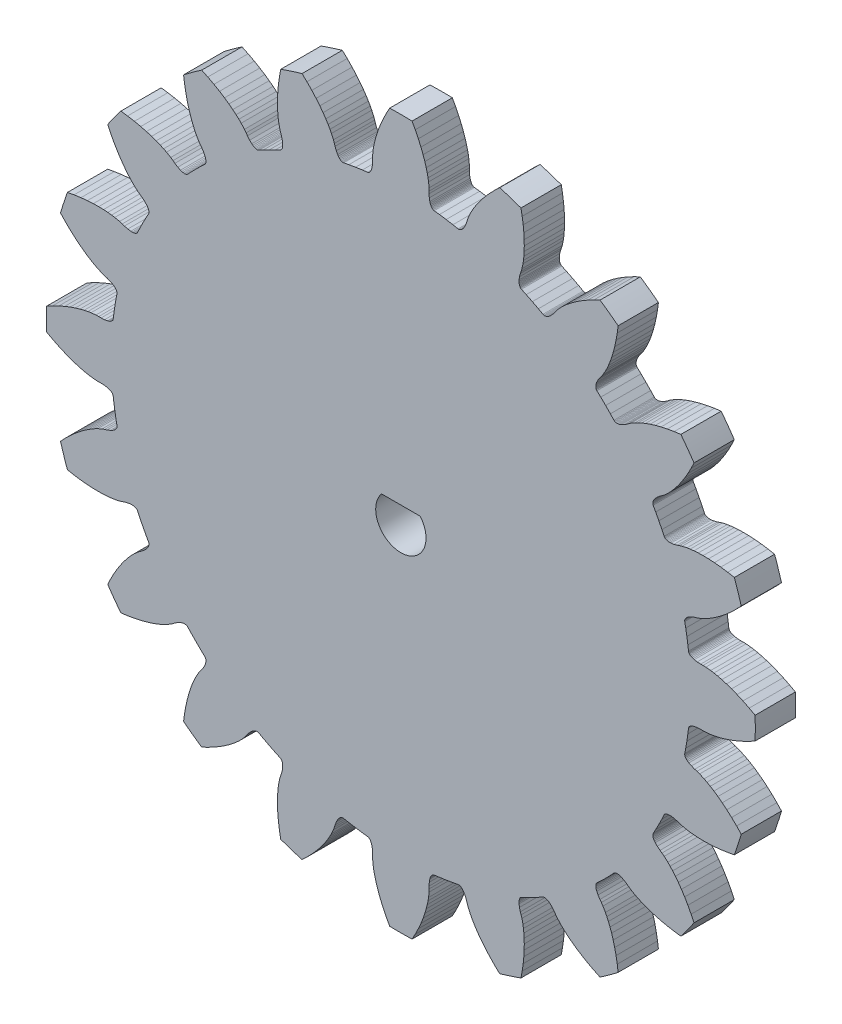
SolidWorks part; units mm, degrees
ref_plane "Front Plane" through (0, 0, 0) normal (0, 0, 1) x (1, 0, 0)
ref_plane "Top Plane" through (0, 0, 0) normal (0, 1, 0) x (1, 0, 0)
ref_plane "Right Plane" through (0, 0, 0) normal (1, 0, 0) x (0, 0, -1)
sketch "Model" plane through (0, 0, 0) normal (0, 0, 1) x (1, 0, 0)
  line L0 (41.6786, 11.6622) -> (41.0581, 11.0595)
  line L1 (41.0581, 11.0595) -> (40.4611, 10.5264)
  line L2 (40.4611, 10.5264) -> (39.8935, 10.0607)
  line L3 (39.8935, 10.0607) -> (39.3607, 9.6597)
  line L4 (39.3607, 9.6597) -> (38.8648, 9.3179)
  line L5 (38.8648, 9.3179) -> (38.4118, 9.033)
  line L6 (38.4118, 9.033) -> (38.0041, 8.7997)
  line L7 (38.0041, 8.7997) -> (37.6455, 8.6139)
  line L8 (37.6455, 8.6139) -> (37.0884, 8.3667)
  line L9 (37.0884, 8.3667) -> (36.7615, 8.2523)
  line L10 (36.7615, 8.2523) -> (36.4807, 8.1681)
  line L11 (36.4807, 8.1681) -> (36.0803, 8.0133)
  line L12 (36.0803, 8.0133) -> (35.757, 7.8422)
  line L13 (35.757, 7.8422) -> (35.6244, 7.7525)
  line L14 (35.6244, 7.7525) -> (35.5112, 7.661)
  line L15 (35.5112, 7.661) -> (35.4174, 7.5686)
  line L16 (35.4174, 7.5686) -> (35.3431, 7.476)
  line L17 (35.3431, 7.476) -> (35.2881, 7.3839)
  line L18 (35.2881, 7.3839) -> (35.2524, 7.2932)
  line L19 (35.2524, 7.2932) -> (35.236, 7.2046)
  line L20 (35.236, 7.2046) -> (35.2423, 7.0979)
  line L21 (35.2423, 7.0979) -> (35.3653, 6.4581)
  line L22 (35.3653, 6.4581) -> (35.5074, 5.6238)
  line L23 (35.5074, 5.6238) -> (35.6301, 4.7864)
  line L24 (35.6301, 4.7864) -> (35.7108, 4.1399)
  line L25 (35.7108, 4.1399) -> (35.7378, 4.0366)
  line L26 (35.7378, 4.0366) -> (35.7808, 3.9574)
  line L27 (35.7808, 3.9574) -> (35.8427, 3.8821)
  line L28 (35.8427, 3.8821) -> (35.9235, 3.8115)
  line L29 (35.9235, 3.8115) -> (36.0228, 3.7464)
  line L30 (36.0228, 3.7464) -> (36.1405, 3.6875)
  line L31 (36.1405, 3.6875) -> (36.2764, 3.6355)
  line L32 (36.2764, 3.6355) -> (36.4303, 3.5911)
  line L33 (36.4303, 3.5911) -> (36.7907, 3.5283)
  line L34 (36.7907, 3.5283) -> (37.2193, 3.5048)
  line L35 (37.2193, 3.5048) -> (37.5124, 3.5115)
  line L36 (37.5124, 3.5115) -> (37.8587, 3.5038)
  line L37 (37.8587, 3.5038) -> (38.4649, 3.4408)
  line L38 (38.4649, 3.4408) -> (38.8633, 3.3749)
  line L39 (38.8633, 3.3749) -> (39.3231, 3.279)
  line L40 (39.3231, 3.279) -> (39.842, 3.148)
  line L41 (39.842, 3.148) -> (40.4192, 2.9762)
  line L42 (40.4192, 2.9762) -> (41.0499, 2.7595)
  line L43 (41.0499, 2.7595) -> (41.7336, 2.492)
  line L44 (41.7336, 2.492) -> (42.4661, 2.1695)
  line L45 (42.4661, 2.1695) -> (43.2425, 1.788)
  line L46 (43.2425, 1.788) -> (43.978, 1.389)
  line L47 (43.978, -1.389) -> (43.2425, -1.788)
  line L48 (43.2425, -1.788) -> (42.4661, -2.1695)
  line L49 (42.4661, -2.1695) -> (41.7336, -2.492)
  line L50 (41.7336, -2.492) -> (41.0499, -2.7595)
  line L51 (41.0499, -2.7595) -> (40.4192, -2.9762)
  line L52 (40.4192, -2.9762) -> (39.842, -3.148)
  line L53 (39.842, -3.148) -> (39.3231, -3.279)
  line L54 (39.3231, -3.279) -> (38.8633, -3.3749)
  line L55 (38.8633, -3.3749) -> (38.4649, -3.4408)
  line L56 (38.4649, -3.4408) -> (37.8587, -3.5038)
  line L57 (37.8587, -3.5038) -> (37.5124, -3.5115)
  line L58 (37.5124, -3.5115) -> (37.2193, -3.5048)
  line L59 (37.2193, -3.5048) -> (36.7907, -3.5283)
  line L60 (36.7907, -3.5283) -> (36.4303, -3.5911)
  line L61 (36.4303, -3.5911) -> (36.2764, -3.6355)
  line L62 (36.2764, -3.6355) -> (36.1405, -3.6875)
  line L63 (36.1405, -3.6875) -> (36.0228, -3.7464)
  line L64 (36.0228, -3.7464) -> (35.9235, -3.8115)
  line L65 (35.9235, -3.8115) -> (35.8427, -3.8821)
  line L66 (35.8427, -3.8821) -> (35.7808, -3.9574)
  line L67 (35.7808, -3.9574) -> (35.7378, -4.0366)
  line L68 (35.7378, -4.0366) -> (35.7108, -4.1399)
  line L69 (35.7108, -4.1399) -> (35.6301, -4.7864)
  line L70 (35.6301, -4.7864) -> (35.5074, -5.6238)
  line L71 (35.5074, -5.6238) -> (35.3653, -6.4581)
  line L72 (35.3653, -6.4581) -> (35.2423, -7.0979)
  line L73 (35.2423, -7.0979) -> (35.236, -7.2046)
  line L74 (35.236, -7.2046) -> (35.2524, -7.2932)
  line L75 (35.2524, -7.2932) -> (35.2881, -7.3839)
  line L76 (35.2881, -7.3839) -> (35.3431, -7.476)
  line L77 (35.3431, -7.476) -> (35.4174, -7.5686)
  line L78 (35.4174, -7.5686) -> (35.5112, -7.661)
  line L79 (35.5112, -7.661) -> (35.6244, -7.7525)
  line L80 (35.6244, -7.7525) -> (35.757, -7.8422)
  line L81 (35.757, -7.8422) -> (36.0803, -8.0133)
  line L82 (36.0803, -8.0133) -> (36.4807, -8.1681)
  line L83 (36.4807, -8.1681) -> (36.7615, -8.2523)
  line L84 (36.7615, -8.2523) -> (37.0884, -8.3667)
  line L85 (37.0884, -8.3667) -> (37.6455, -8.6139)
  line L86 (37.6455, -8.6139) -> (38.0041, -8.7997)
  line L87 (38.0041, -8.7997) -> (38.4118, -9.033)
  line L88 (38.4118, -9.033) -> (38.8648, -9.3179)
  line L89 (38.8648, -9.3179) -> (39.3607, -9.6597)
  line L90 (39.3607, -9.6597) -> (39.8935, -10.0607)
  line L91 (39.8935, -10.0607) -> (40.4611, -10.5264)
  line L92 (40.4611, -10.5264) -> (41.0581, -11.0595)
  line L93 (41.0581, -11.0595) -> (41.6786, -11.6622)
  line L94 (41.6786, -11.6622) -> (42.2548, -12.2689)
  line L95 (41.3963, -14.911) -> (40.5736, -15.0632)
  line L96 (40.5736, -15.0632) -> (39.7173, -15.186)
  line L97 (39.7173, -15.186) -> (38.921, -15.2664)
  line L98 (38.921, -15.2664) -> (38.1881, -15.3095)
  line L99 (38.1881, -15.3095) -> (37.5212, -15.3208)
  line L100 (37.5212, -15.3208) -> (36.9192, -15.3058)
  line L101 (36.9192, -15.3058) -> (36.3852, -15.2701)
  line L102 (36.3852, -15.2701) -> (35.9183, -15.2192)
  line L103 (35.9183, -15.2192) -> (35.519, -15.1587)
  line L104 (35.519, -15.1587) -> (34.923, -15.0313)
  line L105 (34.923, -15.0313) -> (34.5913, -14.9316)
  line L106 (34.5913, -14.9316) -> (34.3146, -14.8347)
  line L107 (34.3146, -14.8347) -> (33.8997, -14.7246)
  line L108 (33.8997, -14.7246) -> (33.5375, -14.673)
  line L109 (33.5375, -14.673) -> (33.3775, -14.6676)
  line L110 (33.3775, -14.6676) -> (33.2322, -14.675)
  line L111 (33.2322, -14.675) -> (33.102, -14.6947)
  line L112 (33.102, -14.6947) -> (32.9874, -14.726)
  line L113 (32.9874, -14.726) -> (32.8888, -14.7681)
  line L114 (32.8888, -14.7681) -> (32.8066, -14.8206)
  line L115 (32.8066, -14.8206) -> (32.7413, -14.8826)
  line L116 (32.7413, -14.8826) -> (32.6837, -14.9726)
  line L117 (32.6837, -14.9726) -> (32.4071, -15.5625)
  line L118 (32.4071, -15.5625) -> (32.0317, -16.321)
  line L119 (32.0317, -16.321) -> (31.6387, -17.0705)
  line L120 (31.6387, -17.0705) -> (31.3241, -17.641)
  line L121 (31.3241, -17.641) -> (31.2851, -17.7405)
  line L122 (31.2851, -17.7405) -> (31.2733, -17.8298)
  line L123 (31.2733, -17.8298) -> (31.2792, -17.9271)
  line L124 (31.2792, -17.9271) -> (31.3031, -18.0317)
  line L125 (31.3031, -18.0317) -> (31.3451, -18.1427)
  line L126 (31.3451, -18.1427) -> (31.4057, -18.2596)
  line L127 (31.4057, -18.2596) -> (31.4851, -18.3816)
  line L128 (31.4851, -18.3816) -> (31.5835, -18.5079)
  line L129 (31.5835, -18.5079) -> (31.8382, -18.7705)
  line L130 (31.8382, -18.7705) -> (32.1711, -19.0415)
  line L131 (32.1711, -19.0415) -> (32.4121, -19.2084)
  line L132 (32.4121, -19.2084) -> (32.6878, -19.4181)
  line L133 (32.6878, -19.4181) -> (33.1412, -19.8254)
  line L134 (33.1412, -19.8254) -> (33.4248, -20.1129)
  line L135 (33.4248, -20.1129) -> (33.7404, -20.4607)
  line L136 (33.7404, -20.4607) -> (34.0832, -20.8718)
  line L137 (34.0832, -20.8718) -> (34.4492, -21.35)
  line L138 (34.4492, -21.35) -> (34.832, -21.8961)
  line L139 (34.832, -21.8961) -> (35.228, -22.5143)
  line L140 (35.228, -22.5143) -> (35.631, -23.2058)
  line L141 (35.631, -23.2058) -> (36.0349, -23.9708)
  line L142 (36.0349, -23.9708) -> (36.3954, -24.7259)
  line L143 (34.7625, -26.9734) -> (33.933, -26.8638)
  line L144 (33.933, -26.8638) -> (33.0806, -26.7161)
  line L145 (33.0806, -26.7161) -> (32.2984, -26.5465)
  line L146 (32.2984, -26.5465) -> (31.5881, -26.361)
  line L147 (31.5881, -26.361) -> (30.9504, -26.1656)
  line L148 (30.9504, -26.1656) -> (30.3825, -25.9653)
  line L149 (30.3825, -25.9653) -> (29.8857, -25.7663)
  line L150 (29.8857, -25.7663) -> (29.4573, -25.5736)
  line L151 (29.4573, -25.5736) -> (29.0963, -25.3927)
  line L152 (29.0963, -25.3927) -> (28.5688, -25.0874)
  line L153 (28.5688, -25.0874) -> (28.2841, -24.8901)
  line L154 (28.2841, -24.8901) -> (28.0509, -24.7124)
  line L155 (28.0509, -24.7124) -> (27.6904, -24.4795)
  line L156 (27.6904, -24.4795) -> (27.3619, -24.3185)
  line L157 (27.3619, -24.3185) -> (27.2114, -24.2639)
  line L158 (27.2114, -24.2639) -> (27.0708, -24.2261)
  line L159 (27.0708, -24.2261) -> (26.941, -24.2046)
  line L160 (26.941, -24.2046) -> (26.8223, -24.1989)
  line L161 (26.8223, -24.1989) -> (26.7155, -24.2085)
  line L162 (26.7155, -24.2085) -> (26.6212, -24.233)
  line L163 (26.6212, -24.233) -> (26.5398, -24.2718)
  line L164 (26.5398, -24.2718) -> (26.4573, -24.3396)
  line L165 (26.4573, -24.3396) -> (26.0119, -24.8151)
  line L166 (26.0119, -24.8151) -> (25.4205, -25.4205)
  line L167 (25.4205, -25.4205) -> (24.8151, -26.0119)
  line L168 (24.8151, -26.0119) -> (24.3396, -26.4573)
  line L169 (24.3396, -26.4573) -> (24.2718, -26.5398)
  line L170 (24.2718, -26.5398) -> (24.233, -26.6212)
  line L171 (24.233, -26.6212) -> (24.2085, -26.7155)
  line L172 (24.2085, -26.7155) -> (24.1989, -26.8223)
  line L173 (24.1989, -26.8223) -> (24.2046, -26.941)
  line L174 (24.2046, -26.941) -> (24.2261, -27.0708)
  line L175 (24.2261, -27.0708) -> (24.2639, -27.2114)
  line L176 (24.2639, -27.2114) -> (24.3185, -27.3619)
  line L177 (24.3185, -27.3619) -> (24.4795, -27.6904)
  line L178 (24.4795, -27.6904) -> (24.7124, -28.0509)
  line L179 (24.7124, -28.0509) -> (24.8901, -28.2841)
  line L180 (24.8901, -28.2841) -> (25.0874, -28.5688)
  line L181 (25.0874, -28.5688) -> (25.3927, -29.0963)
  line L182 (25.3927, -29.0963) -> (25.5736, -29.4573)
  line L183 (25.5736, -29.4573) -> (25.7663, -29.8857)
  line L184 (25.7663, -29.8857) -> (25.9653, -30.3825)
  line L185 (25.9653, -30.3825) -> (26.1656, -30.9504)
  line L186 (26.1656, -30.9504) -> (26.361, -31.5881)
  line L187 (26.361, -31.5881) -> (26.5465, -32.2984)
  line L188 (26.5465, -32.2984) -> (26.7161, -33.0806)
  line L189 (26.7161, -33.0806) -> (26.8638, -33.933)
  line L190 (26.8638, -33.933) -> (26.9734, -34.7625)
  line L191 (24.7259, -36.3954) -> (23.9708, -36.0349)
  line L192 (23.9708, -36.0349) -> (23.2058, -35.631)
  line L193 (23.2058, -35.631) -> (22.5143, -35.228)
  line L194 (22.5143, -35.228) -> (21.8961, -34.832)
  line L195 (21.8961, -34.832) -> (21.35, -34.4492)
  line L196 (21.35, -34.4492) -> (20.8718, -34.0832)
  line L197 (20.8718, -34.0832) -> (20.4607, -33.7404)
  line L198 (20.4607, -33.7404) -> (20.1129, -33.4248)
  line L199 (20.1129, -33.4248) -> (19.8254, -33.1412)
  line L200 (19.8254, -33.1412) -> (19.4181, -32.6878)
  line L201 (19.4181, -32.6878) -> (19.2084, -32.4121)
  line L202 (19.2084, -32.4121) -> (19.0415, -32.1711)
  line L203 (19.0415, -32.1711) -> (18.7705, -31.8382)
  line L204 (18.7705, -31.8382) -> (18.5079, -31.5835)
  line L205 (18.5079, -31.5835) -> (18.3816, -31.4851)
  line L206 (18.3816, -31.4851) -> (18.2596, -31.4057)
  line L207 (18.2596, -31.4057) -> (18.1427, -31.3451)
  line L208 (18.1427, -31.3451) -> (18.0317, -31.3031)
  line L209 (18.0317, -31.3031) -> (17.9271, -31.2792)
  line L210 (17.9271, -31.2792) -> (17.8298, -31.2733)
  line L211 (17.8298, -31.2733) -> (17.7405, -31.2851)
  line L212 (17.7405, -31.2851) -> (17.641, -31.3241)
  line L213 (17.641, -31.3241) -> (17.0705, -31.6387)
  line L214 (17.0705, -31.6387) -> (16.321, -32.0317)
  line L215 (16.321, -32.0317) -> (15.5625, -32.4071)
  line L216 (15.5625, -32.4071) -> (14.9726, -32.6837)
  line L217 (14.9726, -32.6837) -> (14.8826, -32.7413)
  line L218 (14.8826, -32.7413) -> (14.8206, -32.8066)
  line L219 (14.8206, -32.8066) -> (14.7681, -32.8888)
  line L220 (14.7681, -32.8888) -> (14.726, -32.9874)
  line L221 (14.726, -32.9874) -> (14.6947, -33.102)
  line L222 (14.6947, -33.102) -> (14.675, -33.2322)
  line L223 (14.675, -33.2322) -> (14.6676, -33.3775)
  line L224 (14.6676, -33.3775) -> (14.673, -33.5375)
  line L225 (14.673, -33.5375) -> (14.7246, -33.8997)
  line L226 (14.7246, -33.8997) -> (14.8347, -34.3146)
  line L227 (14.8347, -34.3146) -> (14.9316, -34.5913)
  line L228 (14.9316, -34.5913) -> (15.0313, -34.923)
  line L229 (15.0313, -34.923) -> (15.1587, -35.519)
  line L230 (15.1587, -35.519) -> (15.2192, -35.9183)
  line L231 (15.2192, -35.9183) -> (15.2701, -36.3852)
  line L232 (15.2701, -36.3852) -> (15.3058, -36.9192)
  line L233 (15.3058, -36.9192) -> (15.3208, -37.5212)
  line L234 (15.3208, -37.5212) -> (15.3095, -38.1881)
  line L235 (15.3095, -38.1881) -> (15.2664, -38.921)
  line L236 (15.2664, -38.921) -> (15.186, -39.7173)
  line L237 (15.186, -39.7173) -> (15.0632, -40.5736)
  line L238 (15.0632, -40.5736) -> (14.911, -41.3963)
  line L239 (12.2689, -42.2548) -> (11.6622, -41.6786)
  line L240 (11.6622, -41.6786) -> (11.0595, -41.0581)
  line L241 (11.0595, -41.0581) -> (10.5264, -40.4611)
  line L242 (10.5264, -40.4611) -> (10.0607, -39.8935)
  line L243 (10.0607, -39.8935) -> (9.6597, -39.3607)
  line L244 (9.6597, -39.3607) -> (9.3179, -38.8648)
  line L245 (9.3179, -38.8648) -> (9.033, -38.4118)
  line L246 (9.033, -38.4118) -> (8.7997, -38.0041)
  line L247 (8.7997, -38.0041) -> (8.6139, -37.6455)
  line L248 (8.6139, -37.6455) -> (8.3667, -37.0884)
  line L249 (8.3667, -37.0884) -> (8.2523, -36.7615)
  line L250 (8.2523, -36.7615) -> (8.1681, -36.4807)
  line L251 (8.1681, -36.4807) -> (8.0133, -36.0803)
  line L252 (8.0133, -36.0803) -> (7.8422, -35.757)
  line L253 (7.8422, -35.757) -> (7.7525, -35.6244)
  line L254 (7.7525, -35.6244) -> (7.661, -35.5112)
  line L255 (7.661, -35.5112) -> (7.5686, -35.4174)
  line L256 (7.5686, -35.4174) -> (7.476, -35.3431)
  line L257 (7.476, -35.3431) -> (7.3839, -35.2881)
  line L258 (7.3839, -35.2881) -> (7.2932, -35.2524)
  line L259 (7.2932, -35.2524) -> (7.2046, -35.236)
  line L260 (7.2046, -35.236) -> (7.0979, -35.2423)
  line L261 (7.0979, -35.2423) -> (6.4581, -35.3653)
  line L262 (6.4581, -35.3653) -> (5.6238, -35.5074)
  line L263 (5.6238, -35.5074) -> (4.7864, -35.6301)
  line L264 (4.7864, -35.6301) -> (4.1399, -35.7108)
  line L265 (4.1399, -35.7108) -> (4.0366, -35.7378)
  line L266 (4.0366, -35.7378) -> (3.9574, -35.7808)
  line L267 (3.9574, -35.7808) -> (3.8821, -35.8427)
  line L268 (3.8821, -35.8427) -> (3.8115, -35.9235)
  line L269 (3.8115, -35.9235) -> (3.7464, -36.0228)
  line L270 (3.7464, -36.0228) -> (3.6875, -36.1405)
  line L271 (3.6875, -36.1405) -> (3.6355, -36.2764)
  line L272 (3.6355, -36.2764) -> (3.5911, -36.4303)
  line L273 (3.5911, -36.4303) -> (3.5283, -36.7907)
  line L274 (3.5283, -36.7907) -> (3.5048, -37.2193)
  line L275 (3.5048, -37.2193) -> (3.5115, -37.5124)
  line L276 (3.5115, -37.5124) -> (3.5038, -37.8587)
  line L277 (3.5038, -37.8587) -> (3.4408, -38.4649)
  line L278 (3.4408, -38.4649) -> (3.3749, -38.8633)
  line L279 (3.3749, -38.8633) -> (3.279, -39.3231)
  line L280 (3.279, -39.3231) -> (3.148, -39.842)
  line L281 (3.148, -39.842) -> (2.9762, -40.4192)
  line L282 (2.9762, -40.4192) -> (2.7595, -41.0499)
  line L283 (2.7595, -41.0499) -> (2.492, -41.7336)
  line L284 (2.492, -41.7336) -> (2.1695, -42.4661)
  line L285 (2.1695, -42.4661) -> (1.788, -43.2425)
  line L286 (1.788, -43.2425) -> (1.389, -43.978)
  line L287 (-1.389, -43.978) -> (-1.788, -43.2425)
  line L288 (-1.788, -43.2425) -> (-2.1695, -42.4661)
  line L289 (-2.1695, -42.4661) -> (-2.492, -41.7336)
  line L290 (-2.492, -41.7336) -> (-2.7595, -41.0499)
  line L291 (-2.7595, -41.0499) -> (-2.9762, -40.4192)
  line L292 (-2.9762, -40.4192) -> (-3.148, -39.842)
  line L293 (-3.148, -39.842) -> (-3.279, -39.3231)
  line L294 (-3.279, -39.3231) -> (-3.3749, -38.8633)
  line L295 (-3.3749, -38.8633) -> (-3.4408, -38.4649)
  line L296 (-3.4408, -38.4649) -> (-3.5038, -37.8587)
  line L297 (-3.5038, -37.8587) -> (-3.5115, -37.5124)
  line L298 (-3.5115, -37.5124) -> (-3.5048, -37.2193)
  line L299 (-3.5048, -37.2193) -> (-3.5283, -36.7907)
  line L300 (-3.5283, -36.7907) -> (-3.5911, -36.4303)
  line L301 (-3.5911, -36.4303) -> (-3.6355, -36.2764)
  line L302 (-3.6355, -36.2764) -> (-3.6875, -36.1405)
  line L303 (-3.6875, -36.1405) -> (-3.7464, -36.0228)
  line L304 (-3.7464, -36.0228) -> (-3.8115, -35.9235)
  line L305 (-3.8115, -35.9235) -> (-3.8821, -35.8427)
  line L306 (-3.8821, -35.8427) -> (-3.9574, -35.7808)
  line L307 (-3.9574, -35.7808) -> (-4.0366, -35.7378)
  line L308 (-4.0366, -35.7378) -> (-4.1399, -35.7108)
  line L309 (-4.1399, -35.7108) -> (-4.7864, -35.6301)
  line L310 (-4.7864, -35.6301) -> (-5.6238, -35.5074)
  line L311 (-5.6238, -35.5074) -> (-6.4581, -35.3653)
  line L312 (-6.4581, -35.3653) -> (-7.0979, -35.2423)
  line L313 (-7.0979, -35.2423) -> (-7.2046, -35.236)
  line L314 (-7.2046, -35.236) -> (-7.2932, -35.2524)
  line L315 (-7.2932, -35.2524) -> (-7.3839, -35.2881)
  line L316 (-7.3839, -35.2881) -> (-7.476, -35.3431)
  line L317 (-7.476, -35.3431) -> (-7.5686, -35.4174)
  line L318 (-7.5686, -35.4174) -> (-7.661, -35.5112)
  line L319 (-7.661, -35.5112) -> (-7.7525, -35.6244)
  line L320 (-7.7525, -35.6244) -> (-7.8422, -35.757)
  line L321 (-7.8422, -35.757) -> (-8.0133, -36.0803)
  line L322 (-8.0133, -36.0803) -> (-8.1681, -36.4807)
  line L323 (-8.1681, -36.4807) -> (-8.2523, -36.7615)
  line L324 (-8.2523, -36.7615) -> (-8.3667, -37.0884)
  line L325 (-8.3667, -37.0884) -> (-8.6139, -37.6455)
  line L326 (-8.6139, -37.6455) -> (-8.7997, -38.0041)
  line L327 (-8.7997, -38.0041) -> (-9.033, -38.4118)
  line L328 (-9.033, -38.4118) -> (-9.3179, -38.8648)
  line L329 (-9.3179, -38.8648) -> (-9.6597, -39.3607)
  line L330 (-9.6597, -39.3607) -> (-10.0607, -39.8935)
  line L331 (-10.0607, -39.8935) -> (-10.5264, -40.4611)
  line L332 (-10.5264, -40.4611) -> (-11.0595, -41.0581)
  line L333 (-11.0595, -41.0581) -> (-11.6622, -41.6786)
  line L334 (-11.6622, -41.6786) -> (-12.2689, -42.2548)
  line L335 (-14.911, -41.3963) -> (-15.0632, -40.5736)
  line L336 (-15.0632, -40.5736) -> (-15.186, -39.7173)
  line L337 (-15.186, -39.7173) -> (-15.2664, -38.921)
  line L338 (-15.2664, -38.921) -> (-15.3095, -38.1881)
  line L339 (-15.3095, -38.1881) -> (-15.3208, -37.5212)
  line L340 (-15.3208, -37.5212) -> (-15.3058, -36.9192)
  line L341 (-15.3058, -36.9192) -> (-15.2701, -36.3852)
  line L342 (-15.2701, -36.3852) -> (-15.2192, -35.9183)
  line L343 (-15.2192, -35.9183) -> (-15.1587, -35.519)
  line L344 (-15.1587, -35.519) -> (-15.0313, -34.923)
  line L345 (-15.0313, -34.923) -> (-14.9316, -34.5913)
  line L346 (-14.9316, -34.5913) -> (-14.8347, -34.3146)
  line L347 (-14.8347, -34.3146) -> (-14.7246, -33.8997)
  line L348 (-14.7246, -33.8997) -> (-14.673, -33.5375)
  line L349 (-14.673, -33.5375) -> (-14.6676, -33.3775)
  line L350 (-14.6676, -33.3775) -> (-14.675, -33.2322)
  line L351 (-14.675, -33.2322) -> (-14.6947, -33.102)
  line L352 (-14.6947, -33.102) -> (-14.726, -32.9874)
  line L353 (-14.726, -32.9874) -> (-14.7681, -32.8888)
  line L354 (-14.7681, -32.8888) -> (-14.8206, -32.8066)
  line L355 (-14.8206, -32.8066) -> (-14.8826, -32.7413)
  line L356 (-14.8826, -32.7413) -> (-14.9726, -32.6837)
  line L357 (-14.9726, -32.6837) -> (-15.5625, -32.4071)
  line L358 (-15.5625, -32.4071) -> (-16.321, -32.0317)
  line L359 (-16.321, -32.0317) -> (-17.0705, -31.6387)
  line L360 (-17.0705, -31.6387) -> (-17.641, -31.3241)
  line L361 (-17.641, -31.3241) -> (-17.7405, -31.2851)
  line L362 (-17.7405, -31.2851) -> (-17.8298, -31.2733)
  line L363 (-17.8298, -31.2733) -> (-17.9271, -31.2792)
  line L364 (-17.9271, -31.2792) -> (-18.0317, -31.3031)
  line L365 (-18.0317, -31.3031) -> (-18.1427, -31.3451)
  line L366 (-18.1427, -31.3451) -> (-18.2596, -31.4057)
  line L367 (-18.2596, -31.4057) -> (-18.3816, -31.4851)
  line L368 (-18.3816, -31.4851) -> (-18.5079, -31.5835)
  line L369 (-18.5079, -31.5835) -> (-18.7705, -31.8382)
  line L370 (-18.7705, -31.8382) -> (-19.0415, -32.1711)
  line L371 (-19.0415, -32.1711) -> (-19.2084, -32.4121)
  line L372 (-19.2084, -32.4121) -> (-19.4181, -32.6878)
  line L373 (-19.4181, -32.6878) -> (-19.8254, -33.1412)
  line L374 (-19.8254, -33.1412) -> (-20.1129, -33.4248)
  line L375 (-20.1129, -33.4248) -> (-20.4607, -33.7404)
  line L376 (-20.4607, -33.7404) -> (-20.8718, -34.0832)
  line L377 (-20.8718, -34.0832) -> (-21.35, -34.4492)
  line L378 (-21.35, -34.4492) -> (-21.8961, -34.832)
  line L379 (-21.8961, -34.832) -> (-22.5143, -35.228)
  line L380 (-22.5143, -35.228) -> (-23.2058, -35.631)
  line L381 (-23.2058, -35.631) -> (-23.9708, -36.0349)
  line L382 (-23.9708, -36.0349) -> (-24.7259, -36.3954)
  line L383 (-26.9734, -34.7625) -> (-26.8638, -33.933)
  line L384 (-26.8638, -33.933) -> (-26.7161, -33.0806)
  line L385 (-26.7161, -33.0806) -> (-26.5465, -32.2984)
  line L386 (-26.5465, -32.2984) -> (-26.361, -31.5881)
  line L387 (-26.361, -31.5881) -> (-26.1656, -30.9504)
  line L388 (-26.1656, -30.9504) -> (-25.9653, -30.3825)
  line L389 (-25.9653, -30.3825) -> (-25.7663, -29.8857)
  line L390 (-25.7663, -29.8857) -> (-25.5736, -29.4573)
  line L391 (-25.5736, -29.4573) -> (-25.3927, -29.0963)
  line L392 (-25.3927, -29.0963) -> (-25.0874, -28.5688)
  line L393 (-25.0874, -28.5688) -> (-24.8901, -28.2841)
  line L394 (-24.8901, -28.2841) -> (-24.7124, -28.0509)
  line L395 (-24.7124, -28.0509) -> (-24.4795, -27.6904)
  line L396 (-24.4795, -27.6904) -> (-24.3185, -27.3619)
  line L397 (-24.3185, -27.3619) -> (-24.2639, -27.2114)
  line L398 (-24.2639, -27.2114) -> (-24.2261, -27.0708)
  line L399 (-24.2261, -27.0708) -> (-24.2046, -26.941)
  line L400 (-24.2046, -26.941) -> (-24.1989, -26.8223)
  line L401 (-24.1989, -26.8223) -> (-24.2085, -26.7155)
  line L402 (-24.2085, -26.7155) -> (-24.233, -26.6212)
  line L403 (-24.233, -26.6212) -> (-24.2718, -26.5398)
  line L404 (-24.2718, -26.5398) -> (-24.3396, -26.4573)
  line L405 (-24.3396, -26.4573) -> (-24.8151, -26.0119)
  line L406 (-24.8151, -26.0119) -> (-25.4205, -25.4205)
  line L407 (-25.4205, -25.4205) -> (-26.0119, -24.8151)
  line L408 (-26.0119, -24.8151) -> (-26.4573, -24.3396)
  line L409 (-26.4573, -24.3396) -> (-26.5398, -24.2718)
  line L410 (-26.5398, -24.2718) -> (-26.6212, -24.233)
  line L411 (-26.6212, -24.233) -> (-26.7155, -24.2085)
  line L412 (-26.7155, -24.2085) -> (-26.8223, -24.1989)
  line L413 (-26.8223, -24.1989) -> (-26.941, -24.2046)
  line L414 (-26.941, -24.2046) -> (-27.0708, -24.2261)
  line L415 (-27.0708, -24.2261) -> (-27.2114, -24.2639)
  line L416 (-27.2114, -24.2639) -> (-27.3619, -24.3185)
  line L417 (-27.3619, -24.3185) -> (-27.6904, -24.4795)
  line L418 (-27.6904, -24.4795) -> (-28.0509, -24.7124)
  line L419 (-28.0509, -24.7124) -> (-28.2841, -24.8901)
  line L420 (-28.2841, -24.8901) -> (-28.5688, -25.0874)
  line L421 (-28.5688, -25.0874) -> (-29.0963, -25.3927)
  line L422 (-29.0963, -25.3927) -> (-29.4573, -25.5736)
  line L423 (-29.4573, -25.5736) -> (-29.8857, -25.7663)
  line L424 (-29.8857, -25.7663) -> (-30.3825, -25.9653)
  line L425 (-30.3825, -25.9653) -> (-30.9504, -26.1656)
  line L426 (-30.9504, -26.1656) -> (-31.5881, -26.361)
  line L427 (-31.5881, -26.361) -> (-32.2984, -26.5465)
  line L428 (-32.2984, -26.5465) -> (-33.0806, -26.7161)
  line L429 (-33.0806, -26.7161) -> (-33.933, -26.8638)
  line L430 (-33.933, -26.8638) -> (-34.7625, -26.9734)
  line L431 (-36.3954, -24.7259) -> (-36.0349, -23.9708)
  line L432 (-36.0349, -23.9708) -> (-35.631, -23.2058)
  line L433 (-35.631, -23.2058) -> (-35.228, -22.5143)
  line L434 (-35.228, -22.5143) -> (-34.832, -21.8961)
  line L435 (-34.832, -21.8961) -> (-34.4492, -21.35)
  line L436 (-34.4492, -21.35) -> (-34.0832, -20.8718)
  line L437 (-34.0832, -20.8718) -> (-33.7404, -20.4607)
  line L438 (-33.7404, -20.4607) -> (-33.4248, -20.1129)
  line L439 (-33.4248, -20.1129) -> (-33.1412, -19.8254)
  line L440 (-33.1412, -19.8254) -> (-32.6878, -19.4181)
  line L441 (-32.6878, -19.4181) -> (-32.4121, -19.2084)
  line L442 (-32.4121, -19.2084) -> (-32.1711, -19.0415)
  line L443 (-32.1711, -19.0415) -> (-31.8382, -18.7705)
  line L444 (-31.8382, -18.7705) -> (-31.5835, -18.5079)
  line L445 (-31.5835, -18.5079) -> (-31.4851, -18.3816)
  line L446 (-31.4851, -18.3816) -> (-31.4057, -18.2596)
  line L447 (-31.4057, -18.2596) -> (-31.3451, -18.1427)
  line L448 (-31.3451, -18.1427) -> (-31.3031, -18.0317)
  line L449 (-31.3031, -18.0317) -> (-31.2792, -17.9271)
  line L450 (-31.2792, -17.9271) -> (-31.2733, -17.8298)
  line L451 (-31.2733, -17.8298) -> (-31.2851, -17.7405)
  line L452 (-31.2851, -17.7405) -> (-31.3241, -17.641)
  line L453 (-31.3241, -17.641) -> (-31.6387, -17.0705)
  line L454 (-31.6387, -17.0705) -> (-32.0317, -16.321)
  line L455 (-32.0317, -16.321) -> (-32.4071, -15.5625)
  line L456 (-32.4071, -15.5625) -> (-32.6837, -14.9726)
  line L457 (-32.6837, -14.9726) -> (-32.7413, -14.8826)
  line L458 (-32.7413, -14.8826) -> (-32.8066, -14.8206)
  line L459 (-32.8066, -14.8206) -> (-32.8888, -14.7681)
  line L460 (-32.8888, -14.7681) -> (-32.9874, -14.726)
  line L461 (-32.9874, -14.726) -> (-33.102, -14.6947)
  line L462 (-33.102, -14.6947) -> (-33.2322, -14.675)
  line L463 (-33.2322, -14.675) -> (-33.3775, -14.6676)
  line L464 (-33.3775, -14.6676) -> (-33.5375, -14.673)
  line L465 (-33.5375, -14.673) -> (-33.8997, -14.7246)
  line L466 (-33.8997, -14.7246) -> (-34.3146, -14.8347)
  line L467 (-34.3146, -14.8347) -> (-34.5913, -14.9316)
  line L468 (-34.5913, -14.9316) -> (-34.923, -15.0313)
  line L469 (-34.923, -15.0313) -> (-35.519, -15.1587)
  line L470 (-35.519, -15.1587) -> (-35.9183, -15.2192)
  line L471 (-35.9183, -15.2192) -> (-36.3852, -15.2701)
  line L472 (-36.3852, -15.2701) -> (-36.9192, -15.3058)
  line L473 (-36.9192, -15.3058) -> (-37.5212, -15.3208)
  line L474 (-37.5212, -15.3208) -> (-38.1881, -15.3095)
  line L475 (-38.1881, -15.3095) -> (-38.921, -15.2664)
  line L476 (-38.921, -15.2664) -> (-39.7173, -15.186)
  line L477 (-39.7173, -15.186) -> (-40.5736, -15.0632)
  line L478 (-40.5736, -15.0632) -> (-41.3963, -14.911)
  line L479 (-42.2548, -12.2689) -> (-41.6786, -11.6622)
  line L480 (-41.6786, -11.6622) -> (-41.0581, -11.0595)
  line L481 (-41.0581, -11.0595) -> (-40.4611, -10.5264)
  line L482 (-40.4611, -10.5264) -> (-39.8935, -10.0607)
  line L483 (-39.8935, -10.0607) -> (-39.3607, -9.6597)
  line L484 (-39.3607, -9.6597) -> (-38.8648, -9.3179)
  line L485 (-38.8648, -9.3179) -> (-38.4118, -9.033)
  line L486 (-38.4118, -9.033) -> (-38.0041, -8.7997)
  line L487 (-38.0041, -8.7997) -> (-37.6455, -8.6139)
  line L488 (-37.6455, -8.6139) -> (-37.0884, -8.3667)
  line L489 (-37.0884, -8.3667) -> (-36.7615, -8.2523)
  line L490 (-36.7615, -8.2523) -> (-36.4807, -8.1681)
  line L491 (-36.4807, -8.1681) -> (-36.0803, -8.0133)
  line L492 (-36.0803, -8.0133) -> (-35.757, -7.8422)
  line L493 (-35.757, -7.8422) -> (-35.6244, -7.7525)
  line L494 (-35.6244, -7.7525) -> (-35.5112, -7.661)
  line L495 (-35.5112, -7.661) -> (-35.4174, -7.5686)
  line L496 (-35.4174, -7.5686) -> (-35.3431, -7.476)
  line L497 (-35.3431, -7.476) -> (-35.2881, -7.3839)
  line L498 (-35.2881, -7.3839) -> (-35.2524, -7.2932)
  line L499 (-35.2524, -7.2932) -> (-35.236, -7.2046)
  line L500 (-35.236, -7.2046) -> (-35.2423, -7.0979)
  line L501 (-35.2423, -7.0979) -> (-35.3653, -6.4581)
  line L502 (-35.3653, -6.4581) -> (-35.5074, -5.6238)
  line L503 (-35.5074, -5.6238) -> (-35.6301, -4.7864)
  line L504 (-35.6301, -4.7864) -> (-35.7108, -4.1399)
  line L505 (-35.7108, -4.1399) -> (-35.7378, -4.0366)
  line L506 (-35.7378, -4.0366) -> (-35.7808, -3.9574)
  line L507 (-35.7808, -3.9574) -> (-35.8427, -3.8821)
  line L508 (-35.8427, -3.8821) -> (-35.9235, -3.8115)
  line L509 (-35.9235, -3.8115) -> (-36.0228, -3.7464)
  line L510 (-36.0228, -3.7464) -> (-36.1405, -3.6875)
  line L511 (-36.1405, -3.6875) -> (-36.2764, -3.6355)
  line L512 (-36.2764, -3.6355) -> (-36.4303, -3.5911)
  line L513 (-36.4303, -3.5911) -> (-36.7907, -3.5283)
  line L514 (-36.7907, -3.5283) -> (-37.2193, -3.5048)
  line L515 (-37.2193, -3.5048) -> (-37.5124, -3.5115)
  line L516 (-37.5124, -3.5115) -> (-37.8587, -3.5038)
  line L517 (-37.8587, -3.5038) -> (-38.4649, -3.4408)
  line L518 (-38.4649, -3.4408) -> (-38.8633, -3.3749)
  line L519 (-38.8633, -3.3749) -> (-39.3231, -3.279)
  line L520 (-39.3231, -3.279) -> (-39.842, -3.148)
  line L521 (-39.842, -3.148) -> (-40.4192, -2.9762)
  line L522 (-40.4192, -2.9762) -> (-41.0499, -2.7595)
  line L523 (-41.0499, -2.7595) -> (-41.7336, -2.492)
  line L524 (-41.7336, -2.492) -> (-42.4661, -2.1695)
  line L525 (-42.4661, -2.1695) -> (-43.2425, -1.788)
  line L526 (-43.2425, -1.788) -> (-43.978, -1.389)
  line L527 (-43.978, 1.389) -> (-43.2425, 1.788)
  line L528 (-43.2425, 1.788) -> (-42.4661, 2.1695)
  line L529 (-42.4661, 2.1695) -> (-41.7336, 2.492)
  line L530 (-41.7336, 2.492) -> (-41.0499, 2.7595)
  line L531 (-41.0499, 2.7595) -> (-40.4192, 2.9762)
  line L532 (-40.4192, 2.9762) -> (-39.842, 3.148)
  line L533 (-39.842, 3.148) -> (-39.3231, 3.279)
  line L534 (-39.3231, 3.279) -> (-38.8633, 3.3749)
  line L535 (-38.8633, 3.3749) -> (-38.4649, 3.4408)
  line L536 (-38.4649, 3.4408) -> (-37.8587, 3.5038)
  line L537 (-37.8587, 3.5038) -> (-37.5124, 3.5115)
  line L538 (-37.5124, 3.5115) -> (-37.2193, 3.5048)
  line L539 (-37.2193, 3.5048) -> (-36.7907, 3.5283)
  line L540 (-36.7907, 3.5283) -> (-36.4303, 3.5911)
  line L541 (-36.4303, 3.5911) -> (-36.2764, 3.6355)
  line L542 (-36.2764, 3.6355) -> (-36.1405, 3.6875)
  line L543 (-36.1405, 3.6875) -> (-36.0228, 3.7464)
  line L544 (-36.0228, 3.7464) -> (-35.9235, 3.8115)
  line L545 (-35.9235, 3.8115) -> (-35.8427, 3.8821)
  line L546 (-35.8427, 3.8821) -> (-35.7808, 3.9574)
  line L547 (-35.7808, 3.9574) -> (-35.7378, 4.0366)
  line L548 (-35.7378, 4.0366) -> (-35.7108, 4.1399)
  line L549 (-35.7108, 4.1399) -> (-35.6301, 4.7864)
  line L550 (-35.6301, 4.7864) -> (-35.5074, 5.6238)
  line L551 (-35.5074, 5.6238) -> (-35.3653, 6.4581)
  line L552 (-35.3653, 6.4581) -> (-35.2423, 7.0979)
  line L553 (-35.2423, 7.0979) -> (-35.236, 7.2046)
  line L554 (-35.236, 7.2046) -> (-35.2524, 7.2932)
  line L555 (-35.2524, 7.2932) -> (-35.2881, 7.3839)
  line L556 (-35.2881, 7.3839) -> (-35.3431, 7.476)
  line L557 (-35.3431, 7.476) -> (-35.4174, 7.5686)
  line L558 (-35.4174, 7.5686) -> (-35.5112, 7.661)
  line L559 (-35.5112, 7.661) -> (-35.6244, 7.7525)
  line L560 (-35.6244, 7.7525) -> (-35.757, 7.8422)
  line L561 (-35.757, 7.8422) -> (-36.0803, 8.0133)
  line L562 (-36.0803, 8.0133) -> (-36.4807, 8.1681)
  line L563 (-36.4807, 8.1681) -> (-36.7615, 8.2523)
  line L564 (-36.7615, 8.2523) -> (-37.0884, 8.3667)
  line L565 (-37.0884, 8.3667) -> (-37.6455, 8.6139)
  line L566 (-37.6455, 8.6139) -> (-38.0041, 8.7997)
  line L567 (-38.0041, 8.7997) -> (-38.4118, 9.033)
  line L568 (-38.4118, 9.033) -> (-38.8648, 9.3179)
  line L569 (-38.8648, 9.3179) -> (-39.3607, 9.6597)
  line L570 (-39.3607, 9.6597) -> (-39.8935, 10.0607)
  line L571 (-39.8935, 10.0607) -> (-40.4611, 10.5264)
  line L572 (-40.4611, 10.5264) -> (-41.0581, 11.0595)
  line L573 (-41.0581, 11.0595) -> (-41.6786, 11.6622)
  line L574 (-41.6786, 11.6622) -> (-42.2548, 12.2689)
  line L575 (-41.3963, 14.911) -> (-40.5736, 15.0632)
  line L576 (-40.5736, 15.0632) -> (-39.7173, 15.186)
  line L577 (-39.7173, 15.186) -> (-38.921, 15.2664)
  line L578 (-38.921, 15.2664) -> (-38.1881, 15.3095)
  line L579 (-38.1881, 15.3095) -> (-37.5212, 15.3208)
  line L580 (-37.5212, 15.3208) -> (-36.9192, 15.3058)
  line L581 (-36.9192, 15.3058) -> (-36.3852, 15.2701)
  line L582 (-36.3852, 15.2701) -> (-35.9183, 15.2192)
  line L583 (-35.9183, 15.2192) -> (-35.519, 15.1587)
  line L584 (-35.519, 15.1587) -> (-34.923, 15.0313)
  line L585 (-34.923, 15.0313) -> (-34.5913, 14.9316)
  line L586 (-34.5913, 14.9316) -> (-34.3146, 14.8347)
  line L587 (-34.3146, 14.8347) -> (-33.8997, 14.7246)
  line L588 (-33.8997, 14.7246) -> (-33.5375, 14.673)
  line L589 (-33.5375, 14.673) -> (-33.3775, 14.6676)
  line L590 (-33.3775, 14.6676) -> (-33.2322, 14.675)
  line L591 (-33.2322, 14.675) -> (-33.102, 14.6947)
  line L592 (-33.102, 14.6947) -> (-32.9874, 14.726)
  line L593 (-32.9874, 14.726) -> (-32.8888, 14.7681)
  line L594 (-32.8888, 14.7681) -> (-32.8066, 14.8206)
  line L595 (-32.8066, 14.8206) -> (-32.7413, 14.8826)
  line L596 (-32.7413, 14.8826) -> (-32.6837, 14.9726)
  line L597 (-32.6837, 14.9726) -> (-32.4071, 15.5625)
  line L598 (-32.4071, 15.5625) -> (-32.0317, 16.321)
  line L599 (-32.0317, 16.321) -> (-31.6387, 17.0705)
  line L600 (-31.6387, 17.0705) -> (-31.3241, 17.641)
  line L601 (-31.3241, 17.641) -> (-31.2851, 17.7405)
  line L602 (-31.2851, 17.7405) -> (-31.2733, 17.8298)
  line L603 (-31.2733, 17.8298) -> (-31.2792, 17.9271)
  line L604 (-31.2792, 17.9271) -> (-31.3031, 18.0317)
  line L605 (-31.3031, 18.0317) -> (-31.3451, 18.1427)
  line L606 (-31.3451, 18.1427) -> (-31.4057, 18.2596)
  line L607 (-31.4057, 18.2596) -> (-31.4851, 18.3816)
  line L608 (-31.4851, 18.3816) -> (-31.5835, 18.5079)
  line L609 (-31.5835, 18.5079) -> (-31.8382, 18.7705)
  line L610 (-31.8382, 18.7705) -> (-32.1711, 19.0415)
  line L611 (-32.1711, 19.0415) -> (-32.4121, 19.2084)
  line L612 (-32.4121, 19.2084) -> (-32.6878, 19.4181)
  line L613 (-32.6878, 19.4181) -> (-33.1412, 19.8254)
  line L614 (-33.1412, 19.8254) -> (-33.4248, 20.1129)
  line L615 (-33.4248, 20.1129) -> (-33.7404, 20.4607)
  line L616 (-33.7404, 20.4607) -> (-34.0832, 20.8718)
  line L617 (-34.0832, 20.8718) -> (-34.4492, 21.35)
  line L618 (-34.4492, 21.35) -> (-34.832, 21.8961)
  line L619 (-34.832, 21.8961) -> (-35.228, 22.5143)
  line L620 (-35.228, 22.5143) -> (-35.631, 23.2058)
  line L621 (-35.631, 23.2058) -> (-36.0349, 23.9708)
  line L622 (-36.0349, 23.9708) -> (-36.3954, 24.7259)
  line L623 (-34.7625, 26.9734) -> (-33.933, 26.8638)
  line L624 (-33.933, 26.8638) -> (-33.0806, 26.7161)
  line L625 (-33.0806, 26.7161) -> (-32.2984, 26.5465)
  line L626 (-32.2984, 26.5465) -> (-31.5881, 26.361)
  line L627 (-31.5881, 26.361) -> (-30.9504, 26.1656)
  line L628 (-30.9504, 26.1656) -> (-30.3825, 25.9653)
  line L629 (-30.3825, 25.9653) -> (-29.8857, 25.7663)
  line L630 (-29.8857, 25.7663) -> (-29.4573, 25.5736)
  line L631 (-29.4573, 25.5736) -> (-29.0963, 25.3927)
  line L632 (-29.0963, 25.3927) -> (-28.5688, 25.0874)
  line L633 (-28.5688, 25.0874) -> (-28.2841, 24.8901)
  line L634 (-28.2841, 24.8901) -> (-28.0509, 24.7124)
  line L635 (-28.0509, 24.7124) -> (-27.6904, 24.4795)
  line L636 (-27.6904, 24.4795) -> (-27.3619, 24.3185)
  line L637 (-27.3619, 24.3185) -> (-27.2114, 24.2639)
  line L638 (-27.2114, 24.2639) -> (-27.0708, 24.2261)
  line L639 (-27.0708, 24.2261) -> (-26.941, 24.2046)
  line L640 (-26.941, 24.2046) -> (-26.8223, 24.1989)
  line L641 (-26.8223, 24.1989) -> (-26.7155, 24.2085)
  line L642 (-26.7155, 24.2085) -> (-26.6212, 24.233)
  line L643 (-26.6212, 24.233) -> (-26.5398, 24.2718)
  line L644 (-26.5398, 24.2718) -> (-26.4573, 24.3396)
  line L645 (-26.4573, 24.3396) -> (-26.0119, 24.8151)
  line L646 (-26.0119, 24.8151) -> (-25.4205, 25.4205)
  line L647 (-25.4205, 25.4205) -> (-24.8151, 26.0119)
  line L648 (-24.8151, 26.0119) -> (-24.3396, 26.4573)
  line L649 (-24.3396, 26.4573) -> (-24.2718, 26.5398)
  line L650 (-24.2718, 26.5398) -> (-24.233, 26.6212)
  line L651 (-24.233, 26.6212) -> (-24.2085, 26.7155)
  line L652 (-24.2085, 26.7155) -> (-24.1989, 26.8223)
  line L653 (-24.1989, 26.8223) -> (-24.2046, 26.941)
  line L654 (-24.2046, 26.941) -> (-24.2261, 27.0708)
  line L655 (-24.2261, 27.0708) -> (-24.2639, 27.2114)
  line L656 (-24.2639, 27.2114) -> (-24.3185, 27.3619)
  line L657 (-24.3185, 27.3619) -> (-24.4795, 27.6904)
  line L658 (-24.4795, 27.6904) -> (-24.7124, 28.0509)
  line L659 (-24.7124, 28.0509) -> (-24.8901, 28.2841)
  line L660 (-24.8901, 28.2841) -> (-25.0874, 28.5688)
  line L661 (-25.0874, 28.5688) -> (-25.3927, 29.0963)
  line L662 (-25.3927, 29.0963) -> (-25.5736, 29.4573)
  line L663 (-25.5736, 29.4573) -> (-25.7663, 29.8857)
  line L664 (-25.7663, 29.8857) -> (-25.9653, 30.3825)
  line L665 (-25.9653, 30.3825) -> (-26.1656, 30.9504)
  line L666 (-26.1656, 30.9504) -> (-26.361, 31.5881)
  line L667 (-26.361, 31.5881) -> (-26.5465, 32.2984)
  line L668 (-26.5465, 32.2984) -> (-26.7161, 33.0806)
  line L669 (-26.7161, 33.0806) -> (-26.8638, 33.933)
  line L670 (-26.8638, 33.933) -> (-26.9734, 34.7625)
  line L671 (-24.7259, 36.3954) -> (-23.9708, 36.0349)
  line L672 (-23.9708, 36.0349) -> (-23.2058, 35.631)
  line L673 (-23.2058, 35.631) -> (-22.5143, 35.228)
  line L674 (-22.5143, 35.228) -> (-21.8961, 34.832)
  line L675 (-21.8961, 34.832) -> (-21.35, 34.4492)
  line L676 (-21.35, 34.4492) -> (-20.8718, 34.0832)
  line L677 (-20.8718, 34.0832) -> (-20.4607, 33.7404)
  line L678 (-20.4607, 33.7404) -> (-20.1129, 33.4248)
  line L679 (-20.1129, 33.4248) -> (-19.8254, 33.1412)
  line L680 (-19.8254, 33.1412) -> (-19.4181, 32.6878)
  line L681 (-19.4181, 32.6878) -> (-19.2084, 32.4121)
  line L682 (-19.2084, 32.4121) -> (-19.0415, 32.1711)
  line L683 (-19.0415, 32.1711) -> (-18.7705, 31.8382)
  line L684 (-18.7705, 31.8382) -> (-18.5079, 31.5835)
  line L685 (-18.5079, 31.5835) -> (-18.3816, 31.4851)
  line L686 (-18.3816, 31.4851) -> (-18.2596, 31.4057)
  line L687 (-18.2596, 31.4057) -> (-18.1427, 31.3451)
  line L688 (-18.1427, 31.3451) -> (-18.0317, 31.3031)
  line L689 (-18.0317, 31.3031) -> (-17.9271, 31.2792)
  line L690 (-17.9271, 31.2792) -> (-17.8298, 31.2733)
  line L691 (-17.8298, 31.2733) -> (-17.7405, 31.2851)
  line L692 (-17.7405, 31.2851) -> (-17.641, 31.3241)
  line L693 (-17.641, 31.3241) -> (-17.0705, 31.6387)
  line L694 (-17.0705, 31.6387) -> (-16.321, 32.0317)
  line L695 (-16.321, 32.0317) -> (-15.5625, 32.4071)
  line L696 (-15.5625, 32.4071) -> (-14.9726, 32.6837)
  line L697 (-14.9726, 32.6837) -> (-14.8826, 32.7413)
  line L698 (-14.8826, 32.7413) -> (-14.8206, 32.8066)
  line L699 (-14.8206, 32.8066) -> (-14.7681, 32.8888)
  line L700 (-14.7681, 32.8888) -> (-14.726, 32.9874)
  line L701 (-14.726, 32.9874) -> (-14.6947, 33.102)
  line L702 (-14.6947, 33.102) -> (-14.675, 33.2322)
  line L703 (-14.675, 33.2322) -> (-14.6676, 33.3775)
  line L704 (-14.6676, 33.3775) -> (-14.673, 33.5375)
  line L705 (-14.673, 33.5375) -> (-14.7246, 33.8997)
  line L706 (-14.7246, 33.8997) -> (-14.8347, 34.3146)
  line L707 (-14.8347, 34.3146) -> (-14.9316, 34.5913)
  line L708 (-14.9316, 34.5913) -> (-15.0313, 34.923)
  line L709 (-15.0313, 34.923) -> (-15.1587, 35.519)
  line L710 (-15.1587, 35.519) -> (-15.2192, 35.9183)
  line L711 (-15.2192, 35.9183) -> (-15.2701, 36.3852)
  line L712 (-15.2701, 36.3852) -> (-15.3058, 36.9192)
  line L713 (-15.3058, 36.9192) -> (-15.3208, 37.5212)
  line L714 (-15.3208, 37.5212) -> (-15.3095, 38.1881)
  line L715 (-15.3095, 38.1881) -> (-15.2664, 38.921)
  line L716 (-15.2664, 38.921) -> (-15.186, 39.7173)
  line L717 (-15.186, 39.7173) -> (-15.0632, 40.5736)
  line L718 (-15.0632, 40.5736) -> (-14.911, 41.3963)
  line L719 (-12.2689, 42.2548) -> (-11.6622, 41.6786)
  line L720 (-11.6622, 41.6786) -> (-11.0595, 41.0581)
  line L721 (-11.0595, 41.0581) -> (-10.5264, 40.4611)
  line L722 (-10.5264, 40.4611) -> (-10.0607, 39.8935)
  line L723 (-10.0607, 39.8935) -> (-9.6597, 39.3607)
  line L724 (-9.6597, 39.3607) -> (-9.3179, 38.8648)
  line L725 (-9.3179, 38.8648) -> (-9.033, 38.4118)
  line L726 (-9.033, 38.4118) -> (-8.7997, 38.0041)
  line L727 (-8.7997, 38.0041) -> (-8.6139, 37.6455)
  line L728 (-8.6139, 37.6455) -> (-8.3667, 37.0884)
  line L729 (-8.3667, 37.0884) -> (-8.2523, 36.7615)
  line L730 (-8.2523, 36.7615) -> (-8.1681, 36.4807)
  line L731 (-8.1681, 36.4807) -> (-8.0133, 36.0803)
  line L732 (-8.0133, 36.0803) -> (-7.8422, 35.757)
  line L733 (-7.8422, 35.757) -> (-7.7525, 35.6244)
  line L734 (-7.7525, 35.6244) -> (-7.661, 35.5112)
  line L735 (-7.661, 35.5112) -> (-7.5686, 35.4174)
  line L736 (-7.5686, 35.4174) -> (-7.476, 35.3431)
  line L737 (-7.476, 35.3431) -> (-7.3839, 35.2881)
  line L738 (-7.3839, 35.2881) -> (-7.2932, 35.2524)
  line L739 (-7.2932, 35.2524) -> (-7.2046, 35.236)
  line L740 (-7.2046, 35.236) -> (-7.0979, 35.2423)
  line L741 (-7.0979, 35.2423) -> (-6.4581, 35.3653)
  line L742 (-6.4581, 35.3653) -> (-5.6238, 35.5074)
  line L743 (-5.6238, 35.5074) -> (-4.7864, 35.6301)
  line L744 (-4.7864, 35.6301) -> (-4.1399, 35.7108)
  line L745 (-4.1399, 35.7108) -> (-4.0366, 35.7378)
  line L746 (-4.0366, 35.7378) -> (-3.9574, 35.7808)
  line L747 (-3.9574, 35.7808) -> (-3.8821, 35.8427)
  line L748 (-3.8821, 35.8427) -> (-3.8115, 35.9235)
  line L749 (-3.8115, 35.9235) -> (-3.7464, 36.0228)
  line L750 (-3.7464, 36.0228) -> (-3.6875, 36.1405)
  line L751 (-3.6875, 36.1405) -> (-3.6355, 36.2764)
  line L752 (-3.6355, 36.2764) -> (-3.5911, 36.4303)
  line L753 (-3.5911, 36.4303) -> (-3.5283, 36.7907)
  line L754 (-3.5283, 36.7907) -> (-3.5048, 37.2193)
  line L755 (-3.5048, 37.2193) -> (-3.5115, 37.5124)
  line L756 (-3.5115, 37.5124) -> (-3.5038, 37.8587)
  line L757 (-3.5038, 37.8587) -> (-3.4408, 38.4649)
  line L758 (-3.4408, 38.4649) -> (-3.3749, 38.8633)
  line L759 (-3.3749, 38.8633) -> (-3.279, 39.3231)
  line L760 (-3.279, 39.3231) -> (-3.148, 39.842)
  line L761 (-3.148, 39.842) -> (-2.9762, 40.4192)
  line L762 (-2.9762, 40.4192) -> (-2.7595, 41.0499)
  line L763 (-2.7595, 41.0499) -> (-2.492, 41.7336)
  line L764 (-2.492, 41.7336) -> (-2.1695, 42.4661)
  line L765 (-2.1695, 42.4661) -> (-1.788, 43.2425)
  line L766 (-1.788, 43.2425) -> (-1.389, 43.978)
  line L767 (1.389, 43.978) -> (1.788, 43.2425)
  line L768 (1.788, 43.2425) -> (2.1695, 42.4661)
  line L769 (2.1695, 42.4661) -> (2.492, 41.7336)
  line L770 (2.492, 41.7336) -> (2.7595, 41.0499)
  line L771 (2.7595, 41.0499) -> (2.9762, 40.4192)
  line L772 (2.9762, 40.4192) -> (3.148, 39.842)
  line L773 (3.148, 39.842) -> (3.279, 39.3231)
  line L774 (3.279, 39.3231) -> (3.3749, 38.8633)
  line L775 (3.3749, 38.8633) -> (3.4408, 38.4649)
  line L776 (3.4408, 38.4649) -> (3.5038, 37.8587)
  line L777 (3.5038, 37.8587) -> (3.5115, 37.5124)
  line L778 (3.5115, 37.5124) -> (3.5048, 37.2193)
  line L779 (3.5048, 37.2193) -> (3.5283, 36.7907)
  line L780 (3.5283, 36.7907) -> (3.5911, 36.4303)
  line L781 (3.5911, 36.4303) -> (3.6355, 36.2764)
  line L782 (3.6355, 36.2764) -> (3.6875, 36.1405)
  line L783 (3.6875, 36.1405) -> (3.7464, 36.0228)
  line L784 (3.7464, 36.0228) -> (3.8115, 35.9235)
  line L785 (3.8115, 35.9235) -> (3.8821, 35.8427)
  line L786 (3.8821, 35.8427) -> (3.9574, 35.7808)
  line L787 (3.9574, 35.7808) -> (4.0366, 35.7378)
  line L788 (4.0366, 35.7378) -> (4.1399, 35.7108)
  line L789 (4.1399, 35.7108) -> (4.7864, 35.6301)
  line L790 (4.7864, 35.6301) -> (5.6238, 35.5074)
  line L791 (5.6238, 35.5074) -> (6.4581, 35.3653)
  line L792 (6.4581, 35.3653) -> (7.0979, 35.2423)
  line L793 (7.0979, 35.2423) -> (7.2046, 35.236)
  line L794 (7.2046, 35.236) -> (7.2932, 35.2524)
  line L795 (7.2932, 35.2524) -> (7.3839, 35.2881)
  line L796 (7.3839, 35.2881) -> (7.476, 35.3431)
  line L797 (7.476, 35.3431) -> (7.5686, 35.4174)
  line L798 (7.5686, 35.4174) -> (7.661, 35.5112)
  line L799 (7.661, 35.5112) -> (7.7525, 35.6244)
  line L800 (7.7525, 35.6244) -> (7.8422, 35.757)
  line L801 (7.8422, 35.757) -> (8.0133, 36.0803)
  line L802 (8.0133, 36.0803) -> (8.1681, 36.4807)
  line L803 (8.1681, 36.4807) -> (8.2523, 36.7615)
  line L804 (8.2523, 36.7615) -> (8.3667, 37.0884)
  line L805 (8.3667, 37.0884) -> (8.6139, 37.6455)
  line L806 (8.6139, 37.6455) -> (8.7997, 38.0041)
  line L807 (8.7997, 38.0041) -> (9.033, 38.4118)
  line L808 (9.033, 38.4118) -> (9.3179, 38.8648)
  line L809 (9.3179, 38.8648) -> (9.6597, 39.3607)
  line L810 (9.6597, 39.3607) -> (10.0607, 39.8935)
  line L811 (10.0607, 39.8935) -> (10.5264, 40.4611)
  line L812 (10.5264, 40.4611) -> (11.0595, 41.0581)
  line L813 (11.0595, 41.0581) -> (11.6622, 41.6786)
  line L814 (11.6622, 41.6786) -> (12.2689, 42.2548)
  line L815 (14.911, 41.3963) -> (15.0632, 40.5736)
  line L816 (15.0632, 40.5736) -> (15.186, 39.7173)
  line L817 (15.186, 39.7173) -> (15.2664, 38.921)
  line L818 (15.2664, 38.921) -> (15.3095, 38.1881)
  line L819 (15.3095, 38.1881) -> (15.3208, 37.5212)
  line L820 (15.3208, 37.5212) -> (15.3058, 36.9192)
  line L821 (15.3058, 36.9192) -> (15.2701, 36.3852)
  line L822 (15.2701, 36.3852) -> (15.2192, 35.9183)
  line L823 (15.2192, 35.9183) -> (15.1587, 35.519)
  line L824 (15.1587, 35.519) -> (15.0313, 34.923)
  line L825 (15.0313, 34.923) -> (14.9316, 34.5913)
  line L826 (14.9316, 34.5913) -> (14.8347, 34.3146)
  line L827 (14.8347, 34.3146) -> (14.7246, 33.8997)
  line L828 (14.7246, 33.8997) -> (14.673, 33.5375)
  line L829 (14.673, 33.5375) -> (14.6676, 33.3775)
  line L830 (14.6676, 33.3775) -> (14.675, 33.2322)
  line L831 (14.675, 33.2322) -> (14.6947, 33.102)
  line L832 (14.6947, 33.102) -> (14.726, 32.9874)
  line L833 (14.726, 32.9874) -> (14.7681, 32.8888)
  line L834 (14.7681, 32.8888) -> (14.8206, 32.8066)
  line L835 (14.8206, 32.8066) -> (14.8826, 32.7413)
  line L836 (14.8826, 32.7413) -> (14.9726, 32.6837)
  line L837 (14.9726, 32.6837) -> (15.5625, 32.4071)
  line L838 (15.5625, 32.4071) -> (16.321, 32.0317)
  line L839 (16.321, 32.0317) -> (17.0705, 31.6387)
  line L840 (17.0705, 31.6387) -> (17.641, 31.3241)
  line L841 (17.641, 31.3241) -> (17.7405, 31.2851)
  line L842 (17.7405, 31.2851) -> (17.8298, 31.2733)
  line L843 (17.8298, 31.2733) -> (17.9271, 31.2792)
  line L844 (17.9271, 31.2792) -> (18.0317, 31.3031)
  line L845 (18.0317, 31.3031) -> (18.1427, 31.3451)
  line L846 (18.1427, 31.3451) -> (18.2596, 31.4057)
  line L847 (18.2596, 31.4057) -> (18.3816, 31.4851)
  line L848 (18.3816, 31.4851) -> (18.5079, 31.5835)
  line L849 (18.5079, 31.5835) -> (18.7705, 31.8382)
  line L850 (18.7705, 31.8382) -> (19.0415, 32.1711)
  line L851 (19.0415, 32.1711) -> (19.2084, 32.4121)
  line L852 (19.2084, 32.4121) -> (19.4181, 32.6878)
  line L853 (19.4181, 32.6878) -> (19.8254, 33.1412)
  line L854 (19.8254, 33.1412) -> (20.1129, 33.4248)
  line L855 (20.1129, 33.4248) -> (20.4607, 33.7404)
  line L856 (20.4607, 33.7404) -> (20.8718, 34.0832)
  line L857 (20.8718, 34.0832) -> (21.35, 34.4492)
  line L858 (21.35, 34.4492) -> (21.8961, 34.832)
  line L859 (21.8961, 34.832) -> (22.5143, 35.228)
  line L860 (22.5143, 35.228) -> (23.2058, 35.631)
  line L861 (23.2058, 35.631) -> (23.9708, 36.0349)
  line L862 (23.9708, 36.0349) -> (24.7259, 36.3954)
  line L863 (26.9734, 34.7625) -> (26.8638, 33.933)
  line L864 (26.8638, 33.933) -> (26.7161, 33.0806)
  line L865 (26.7161, 33.0806) -> (26.5465, 32.2984)
  line L866 (26.5465, 32.2984) -> (26.361, 31.5881)
  line L867 (26.361, 31.5881) -> (26.1656, 30.9504)
  line L868 (26.1656, 30.9504) -> (25.9653, 30.3825)
  line L869 (25.9653, 30.3825) -> (25.7663, 29.8857)
  line L870 (25.7663, 29.8857) -> (25.5736, 29.4573)
  line L871 (25.5736, 29.4573) -> (25.3927, 29.0963)
  line L872 (25.3927, 29.0963) -> (25.0874, 28.5688)
  line L873 (25.0874, 28.5688) -> (24.8901, 28.2841)
  line L874 (24.8901, 28.2841) -> (24.7124, 28.0509)
  line L875 (24.7124, 28.0509) -> (24.4795, 27.6904)
  line L876 (24.4795, 27.6904) -> (24.3185, 27.3619)
  line L877 (24.3185, 27.3619) -> (24.2639, 27.2114)
  line L878 (24.2639, 27.2114) -> (24.2261, 27.0708)
  line L879 (24.2261, 27.0708) -> (24.2046, 26.941)
  line L880 (24.2046, 26.941) -> (24.1989, 26.8223)
  line L881 (24.1989, 26.8223) -> (24.2085, 26.7155)
  line L882 (24.2085, 26.7155) -> (24.233, 26.6212)
  line L883 (24.233, 26.6212) -> (24.2718, 26.5398)
  line L884 (24.2718, 26.5398) -> (24.3396, 26.4573)
  line L885 (24.3396, 26.4573) -> (24.8151, 26.0119)
  line L886 (24.8151, 26.0119) -> (25.4205, 25.4205)
  line L887 (25.4205, 25.4205) -> (26.0119, 24.8151)
  line L888 (26.0119, 24.8151) -> (26.4573, 24.3396)
  line L889 (26.4573, 24.3396) -> (26.5398, 24.2718)
  line L890 (26.5398, 24.2718) -> (26.6212, 24.233)
  line L891 (26.6212, 24.233) -> (26.7155, 24.2085)
  line L892 (26.7155, 24.2085) -> (26.8223, 24.1989)
  line L893 (26.8223, 24.1989) -> (26.941, 24.2046)
  line L894 (26.941, 24.2046) -> (27.0708, 24.2261)
  line L895 (27.0708, 24.2261) -> (27.2114, 24.2639)
  line L896 (27.2114, 24.2639) -> (27.3619, 24.3185)
  line L897 (27.3619, 24.3185) -> (27.6904, 24.4795)
  line L898 (27.6904, 24.4795) -> (28.0509, 24.7124)
  line L899 (28.0509, 24.7124) -> (28.2841, 24.8901)
  line L900 (28.2841, 24.8901) -> (28.5688, 25.0874)
  line L901 (28.5688, 25.0874) -> (29.0963, 25.3927)
  line L902 (29.0963, 25.3927) -> (29.4573, 25.5736)
  line L903 (29.4573, 25.5736) -> (29.8857, 25.7663)
  line L904 (29.8857, 25.7663) -> (30.3825, 25.9653)
  line L905 (30.3825, 25.9653) -> (30.9504, 26.1656)
  line L906 (30.9504, 26.1656) -> (31.5881, 26.361)
  line L907 (31.5881, 26.361) -> (32.2984, 26.5465)
  line L908 (32.2984, 26.5465) -> (33.0806, 26.7161)
  line L909 (33.0806, 26.7161) -> (33.933, 26.8638)
  line L910 (33.933, 26.8638) -> (34.7625, 26.9734)
  line L911 (36.3954, 24.7259) -> (36.0349, 23.9708)
  line L912 (36.0349, 23.9708) -> (35.631, 23.2058)
  line L913 (35.631, 23.2058) -> (35.228, 22.5143)
  line L914 (35.228, 22.5143) -> (34.832, 21.8961)
  line L915 (34.832, 21.8961) -> (34.4492, 21.35)
  line L916 (34.4492, 21.35) -> (34.0832, 20.8718)
  line L917 (34.0832, 20.8718) -> (33.7404, 20.4607)
  line L918 (33.7404, 20.4607) -> (33.4248, 20.1129)
  line L919 (33.4248, 20.1129) -> (33.1412, 19.8254)
  line L920 (33.1412, 19.8254) -> (32.6878, 19.4181)
  line L921 (32.6878, 19.4181) -> (32.4121, 19.2084)
  line L922 (32.4121, 19.2084) -> (32.1711, 19.0415)
  line L923 (32.1711, 19.0415) -> (31.8382, 18.7705)
  line L924 (31.8382, 18.7705) -> (31.5835, 18.5079)
  line L925 (31.5835, 18.5079) -> (31.4851, 18.3816)
  line L926 (31.4851, 18.3816) -> (31.4057, 18.2596)
  line L927 (31.4057, 18.2596) -> (31.3451, 18.1427)
  line L928 (31.3451, 18.1427) -> (31.3031, 18.0317)
  line L929 (31.3031, 18.0317) -> (31.2792, 17.9271)
  line L930 (31.2792, 17.9271) -> (31.2733, 17.8298)
  line L931 (31.2733, 17.8298) -> (31.2851, 17.7405)
  line L932 (31.2851, 17.7405) -> (31.3241, 17.641)
  line L933 (31.3241, 17.641) -> (31.6387, 17.0705)
  line L934 (31.6387, 17.0705) -> (32.0317, 16.321)
  line L935 (32.0317, 16.321) -> (32.4071, 15.5625)
  line L936 (32.4071, 15.5625) -> (32.6837, 14.9726)
  line L937 (32.6837, 14.9726) -> (32.7413, 14.8826)
  line L938 (32.7413, 14.8826) -> (32.8066, 14.8206)
  line L939 (32.8066, 14.8206) -> (32.8888, 14.7681)
  line L940 (32.8888, 14.7681) -> (32.9874, 14.726)
  line L941 (32.9874, 14.726) -> (33.102, 14.6947)
  line L942 (33.102, 14.6947) -> (33.2322, 14.675)
  line L943 (33.2322, 14.675) -> (33.3775, 14.6676)
  line L944 (33.3775, 14.6676) -> (33.5375, 14.673)
  line L945 (33.5375, 14.673) -> (33.8997, 14.7246)
  line L946 (33.8997, 14.7246) -> (34.3146, 14.8347)
  line L947 (34.3146, 14.8347) -> (34.5913, 14.9316)
  line L948 (34.5913, 14.9316) -> (34.923, 15.0313)
  line L949 (34.923, 15.0313) -> (35.519, 15.1587)
  line L950 (35.519, 15.1587) -> (35.9183, 15.2192)
  line L951 (35.9183, 15.2192) -> (36.3852, 15.2701)
  line L952 (36.3852, 15.2701) -> (36.9192, 15.3058)
  line L953 (36.9192, 15.3058) -> (37.5212, 15.3208)
  line L954 (37.5212, 15.3208) -> (38.1881, 15.3095)
  line L955 (38.1881, 15.3095) -> (38.921, 15.2664)
  line L956 (38.921, 15.2664) -> (39.7173, 15.186)
  line L957 (39.7173, 15.186) -> (40.5736, 15.0632)
  line L958 (40.5736, 15.0632) -> (41.3963, 14.911)
  line L959 (42.2548, 12.2689) -> (41.6786, 11.6622)
  line L960 (41.6786, 11.6622) -> (41.0581, 11.0595)
  line L961 (41.0581, 11.0595) -> (40.4611, 10.5264)
  line L962 (40.4611, 10.5264) -> (39.8935, 10.0607)
  line L963 (39.8935, 10.0607) -> (39.3607, 9.6597)
  line L964 (39.3607, 9.6597) -> (38.8648, 9.3179)
  line L965 (38.8648, 9.3179) -> (38.4118, 9.033)
  line L966 (38.4118, 9.033) -> (38.0041, 8.7997)
  line L967 (38.0041, 8.7997) -> (37.6455, 8.6139)
  line L968 (37.6455, 8.6139) -> (37.0884, 8.3667)
  line L969 (37.0884, 8.3667) -> (36.7615, 8.2523)
  line L970 (36.7615, 8.2523) -> (36.4807, 8.1681)
  line L971 (36.4807, 8.1681) -> (36.0803, 8.0133)
  line L972 (36.0803, 8.0133) -> (35.757, 7.8422)
  line L973 (35.757, 7.8422) -> (35.6244, 7.7525)
  line L974 (35.6244, 7.7525) -> (35.5112, 7.661)
  line L975 (35.5112, 7.661) -> (35.4174, 7.5686)
  line L976 (35.4174, 7.5686) -> (35.3431, 7.476)
  line L977 (35.3431, 7.476) -> (35.2881, 7.3839)
  line L978 (35.2881, 7.3839) -> (35.2524, 7.2932)
  line L979 (35.2524, 7.2932) -> (35.236, 7.2046)
  line L980 (35.236, 7.2046) -> (35.2423, 7.0979)
  line L981 (35.2423, 7.0979) -> (35.3653, 6.4581)
  line L982 (35.3653, 6.4581) -> (35.5074, 5.6238)
  line L983 (35.5074, 5.6238) -> (35.6301, 4.7864)
  line L984 (35.6301, 4.7864) -> (35.7108, 4.1399)
  line L985 (35.7108, 4.1399) -> (35.7378, 4.0366)
  line L986 (35.7378, 4.0366) -> (35.7808, 3.9574)
  line L987 (35.7808, 3.9574) -> (35.8427, 3.8821)
  line L988 (35.8427, 3.8821) -> (35.9235, 3.8115)
  line L989 (35.9235, 3.8115) -> (36.0228, 3.7464)
  line L990 (36.0228, 3.7464) -> (36.1405, 3.6875)
  line L991 (36.1405, 3.6875) -> (36.2764, 3.6355)
  line L992 (36.2764, 3.6355) -> (36.4303, 3.5911)
  line L993 (36.4303, 3.5911) -> (36.7907, 3.5283)
  line L994 (36.7907, 3.5283) -> (37.2193, 3.5048)
  line L995 (37.2193, 3.5048) -> (37.5124, 3.5115)
  line L996 (37.5124, 3.5115) -> (37.8587, 3.5038)
  line L997 (37.8587, 3.5038) -> (38.4649, 3.4408)
  line L998 (38.4649, 3.4408) -> (38.8633, 3.3749)
  line L999 (38.8633, 3.3749) -> (39.3231, 3.279)
  line L1000 (39.3231, 3.279) -> (39.842, 3.148)
  line L1001 (39.842, 3.148) -> (40.4192, 2.9762)
  line L1002 (40.4192, 2.9762) -> (41.0499, 2.7595)
  line L1003 (41.0499, 2.7595) -> (41.7336, 2.492)
  line L1004 (41.7336, 2.492) -> (42.4661, 2.1695)
  line L1005 (42.4661, 2.1695) -> (43.2425, 1.788)
  line L1006 (43.2425, 1.788) -> (43.978, 1.389)
  line L1007 (43.978, -1.389) -> (43.2425, -1.788)
  line L1008 (43.2425, -1.788) -> (42.4661, -2.1695)
  line L1009 (42.4661, -2.1695) -> (41.7336, -2.492)
  line L1010 (41.7336, -2.492) -> (41.0499, -2.7595)
  line L1011 (41.0499, -2.7595) -> (40.4192, -2.9762)
  line L1012 (40.4192, -2.9762) -> (39.842, -3.148)
  line L1013 (39.842, -3.148) -> (39.3231, -3.279)
  line L1014 (39.3231, -3.279) -> (38.8633, -3.3749)
  line L1015 (38.8633, -3.3749) -> (38.4649, -3.4408)
  line L1016 (38.4649, -3.4408) -> (37.8587, -3.5038)
  line L1017 (37.8587, -3.5038) -> (37.5124, -3.5115)
  line L1018 (37.5124, -3.5115) -> (37.2193, -3.5048)
  line L1019 (37.2193, -3.5048) -> (36.7907, -3.5283)
  line L1020 (36.7907, -3.5283) -> (36.4303, -3.5911)
  line L1021 (36.4303, -3.5911) -> (36.2764, -3.6355)
  line L1022 (36.2764, -3.6355) -> (36.1405, -3.6875)
  line L1023 (36.1405, -3.6875) -> (36.0228, -3.7464)
  line L1024 (36.0228, -3.7464) -> (35.9235, -3.8115)
  line L1025 (35.9235, -3.8115) -> (35.8427, -3.8821)
  line L1026 (35.8427, -3.8821) -> (35.7808, -3.9574)
  line L1027 (35.7808, -3.9574) -> (35.7378, -4.0366)
  line L1028 (35.7378, -4.0366) -> (35.7108, -4.1399)
  line L1029 (35.7108, -4.1399) -> (35.6301, -4.7864)
  line L1030 (35.6301, -4.7864) -> (35.5074, -5.6238)
  line L1031 (35.5074, -5.6238) -> (35.3653, -6.4581)
  line L1032 (35.3653, -6.4581) -> (35.2423, -7.0979)
  line L1033 (35.2423, -7.0979) -> (35.236, -7.2046)
  line L1034 (35.236, -7.2046) -> (35.2524, -7.2932)
  line L1035 (35.2524, -7.2932) -> (35.2881, -7.3839)
  line L1036 (35.2881, -7.3839) -> (35.3431, -7.476)
  line L1037 (35.3431, -7.476) -> (35.4174, -7.5686)
  line L1038 (35.4174, -7.5686) -> (35.5112, -7.661)
  line L1039 (35.5112, -7.661) -> (35.6244, -7.7525)
  line L1040 (35.6244, -7.7525) -> (35.757, -7.8422)
  line L1041 (35.757, -7.8422) -> (36.0803, -8.0133)
  line L1042 (36.0803, -8.0133) -> (36.4807, -8.1681)
  line L1043 (36.4807, -8.1681) -> (36.7615, -8.2523)
  line L1044 (36.7615, -8.2523) -> (37.0884, -8.3667)
  line L1045 (37.0884, -8.3667) -> (37.6455, -8.6139)
  line L1046 (37.6455, -8.6139) -> (38.0041, -8.7997)
  line L1047 (38.0041, -8.7997) -> (38.4118, -9.033)
  line L1048 (38.4118, -9.033) -> (38.8648, -9.3179)
  line L1049 (38.8648, -9.3179) -> (39.3607, -9.6597)
  line L1050 (39.3607, -9.6597) -> (39.8935, -10.0607)
  line L1051 (39.8935, -10.0607) -> (40.4611, -10.5264)
  line L1052 (40.4611, -10.5264) -> (41.0581, -11.0595)
  line L1053 (41.0581, -11.0595) -> (41.6786, -11.6622)
  line L1054 (41.6786, -11.6622) -> (42.2548, -12.2689)
  line L1055 (41.3963, -14.911) -> (40.5736, -15.0632)
  line L1056 (40.5736, -15.0632) -> (39.7173, -15.186)
  line L1057 (39.7173, -15.186) -> (38.921, -15.2664)
  line L1058 (38.921, -15.2664) -> (38.1881, -15.3095)
  line L1059 (38.1881, -15.3095) -> (37.5212, -15.3208)
  line L1060 (37.5212, -15.3208) -> (36.9192, -15.3058)
  line L1061 (36.9192, -15.3058) -> (36.3852, -15.2701)
  line L1062 (36.3852, -15.2701) -> (35.9183, -15.2192)
  line L1063 (35.9183, -15.2192) -> (35.519, -15.1587)
  line L1064 (35.519, -15.1587) -> (34.923, -15.0313)
  line L1065 (34.923, -15.0313) -> (34.5913, -14.9316)
  line L1066 (34.5913, -14.9316) -> (34.3146, -14.8347)
  line L1067 (34.3146, -14.8347) -> (33.8997, -14.7246)
  line L1068 (33.8997, -14.7246) -> (33.5375, -14.673)
  line L1069 (33.5375, -14.673) -> (33.3775, -14.6676)
  line L1070 (33.3775, -14.6676) -> (33.2322, -14.675)
  line L1071 (33.2322, -14.675) -> (33.102, -14.6947)
  line L1072 (33.102, -14.6947) -> (32.9874, -14.726)
  line L1073 (32.9874, -14.726) -> (32.8888, -14.7681)
  line L1074 (32.8888, -14.7681) -> (32.8066, -14.8206)
  line L1075 (32.8066, -14.8206) -> (32.7413, -14.8826)
  line L1076 (32.7413, -14.8826) -> (32.6837, -14.9726)
  line L1077 (32.6837, -14.9726) -> (32.4071, -15.5625)
  line L1078 (32.4071, -15.5625) -> (32.0317, -16.321)
  line L1079 (32.0317, -16.321) -> (31.6387, -17.0705)
  line L1080 (31.6387, -17.0705) -> (31.3241, -17.641)
  line L1081 (31.3241, -17.641) -> (31.2851, -17.7405)
  line L1082 (31.2851, -17.7405) -> (31.2733, -17.8298)
  line L1083 (31.2733, -17.8298) -> (31.2792, -17.9271)
  line L1084 (31.2792, -17.9271) -> (31.3031, -18.0317)
  line L1085 (31.3031, -18.0317) -> (31.3451, -18.1427)
  line L1086 (31.3451, -18.1427) -> (31.4057, -18.2596)
  line L1087 (31.4057, -18.2596) -> (31.4851, -18.3816)
  line L1088 (31.4851, -18.3816) -> (31.5835, -18.5079)
  line L1089 (31.5835, -18.5079) -> (31.8382, -18.7705)
  line L1090 (31.8382, -18.7705) -> (32.1711, -19.0415)
  line L1091 (32.1711, -19.0415) -> (32.4121, -19.2084)
  line L1092 (32.4121, -19.2084) -> (32.6878, -19.4181)
  line L1093 (32.6878, -19.4181) -> (33.1412, -19.8254)
  line L1094 (33.1412, -19.8254) -> (33.4248, -20.1129)
  line L1095 (33.4248, -20.1129) -> (33.7404, -20.4607)
  line L1096 (33.7404, -20.4607) -> (34.0832, -20.8718)
  line L1097 (34.0832, -20.8718) -> (34.4492, -21.35)
  line L1098 (34.4492, -21.35) -> (34.832, -21.8961)
  line L1099 (34.832, -21.8961) -> (35.228, -22.5143)
  line L1100 (35.228, -22.5143) -> (35.631, -23.2058)
  line L1101 (35.631, -23.2058) -> (36.0349, -23.9708)
  line L1102 (36.0349, -23.9708) -> (36.3954, -24.7259)
  line L1103 (34.7625, -26.9734) -> (33.933, -26.8638)
  line L1104 (33.933, -26.8638) -> (33.0806, -26.7161)
  line L1105 (33.0806, -26.7161) -> (32.2984, -26.5465)
  line L1106 (32.2984, -26.5465) -> (31.5881, -26.361)
  line L1107 (31.5881, -26.361) -> (30.9504, -26.1656)
  line L1108 (30.9504, -26.1656) -> (30.3825, -25.9653)
  line L1109 (30.3825, -25.9653) -> (29.8857, -25.7663)
  line L1110 (29.8857, -25.7663) -> (29.4573, -25.5736)
  line L1111 (29.4573, -25.5736) -> (29.0963, -25.3927)
  line L1112 (29.0963, -25.3927) -> (28.5688, -25.0874)
  line L1113 (28.5688, -25.0874) -> (28.2841, -24.8901)
  line L1114 (28.2841, -24.8901) -> (28.0509, -24.7124)
  line L1115 (28.0509, -24.7124) -> (27.6904, -24.4795)
  line L1116 (27.6904, -24.4795) -> (27.3619, -24.3185)
  line L1117 (27.3619, -24.3185) -> (27.2114, -24.2639)
  line L1118 (27.2114, -24.2639) -> (27.0708, -24.2261)
  line L1119 (27.0708, -24.2261) -> (26.941, -24.2046)
  line L1120 (26.941, -24.2046) -> (26.8223, -24.1989)
  line L1121 (26.8223, -24.1989) -> (26.7155, -24.2085)
  line L1122 (26.7155, -24.2085) -> (26.6212, -24.233)
  line L1123 (26.6212, -24.233) -> (26.5398, -24.2718)
  line L1124 (26.5398, -24.2718) -> (26.4573, -24.3396)
  line L1125 (26.4573, -24.3396) -> (26.0119, -24.8151)
  line L1126 (26.0119, -24.8151) -> (25.4205, -25.4205)
  line L1127 (25.4205, -25.4205) -> (24.8151, -26.0119)
  line L1128 (24.8151, -26.0119) -> (24.3396, -26.4573)
  line L1129 (24.3396, -26.4573) -> (24.2718, -26.5398)
  line L1130 (24.2718, -26.5398) -> (24.233, -26.6212)
  line L1131 (24.233, -26.6212) -> (24.2085, -26.7155)
  line L1132 (24.2085, -26.7155) -> (24.1989, -26.8223)
  line L1133 (24.1989, -26.8223) -> (24.2046, -26.941)
  line L1134 (24.2046, -26.941) -> (24.2261, -27.0708)
  line L1135 (24.2261, -27.0708) -> (24.2639, -27.2114)
  line L1136 (24.2639, -27.2114) -> (24.3185, -27.3619)
  line L1137 (24.3185, -27.3619) -> (24.4795, -27.6904)
  line L1138 (24.4795, -27.6904) -> (24.7124, -28.0509)
  line L1139 (24.7124, -28.0509) -> (24.8901, -28.2841)
  line L1140 (24.8901, -28.2841) -> (25.0874, -28.5688)
  line L1141 (25.0874, -28.5688) -> (25.3927, -29.0963)
  line L1142 (25.3927, -29.0963) -> (25.5736, -29.4573)
  line L1143 (25.5736, -29.4573) -> (25.7663, -29.8857)
  line L1144 (25.7663, -29.8857) -> (25.9653, -30.3825)
  line L1145 (25.9653, -30.3825) -> (26.1656, -30.9504)
  line L1146 (26.1656, -30.9504) -> (26.361, -31.5881)
  line L1147 (26.361, -31.5881) -> (26.5465, -32.2984)
  line L1148 (26.5465, -32.2984) -> (26.7161, -33.0806)
  line L1149 (26.7161, -33.0806) -> (26.8638, -33.933)
  line L1150 (26.8638, -33.933) -> (26.9734, -34.7625)
  line L1151 (24.7259, -36.3954) -> (23.9708, -36.0349)
  line L1152 (23.9708, -36.0349) -> (23.2058, -35.631)
  line L1153 (23.2058, -35.631) -> (22.5143, -35.228)
  line L1154 (22.5143, -35.228) -> (21.8961, -34.832)
  line L1155 (21.8961, -34.832) -> (21.35, -34.4492)
  line L1156 (21.35, -34.4492) -> (20.8718, -34.0832)
  line L1157 (20.8718, -34.0832) -> (20.4607, -33.7404)
  line L1158 (20.4607, -33.7404) -> (20.1129, -33.4248)
  line L1159 (20.1129, -33.4248) -> (19.8254, -33.1412)
  line L1160 (19.8254, -33.1412) -> (19.4181, -32.6878)
  line L1161 (19.4181, -32.6878) -> (19.2084, -32.4121)
  line L1162 (19.2084, -32.4121) -> (19.0415, -32.1711)
  line L1163 (19.0415, -32.1711) -> (18.7705, -31.8382)
  line L1164 (18.7705, -31.8382) -> (18.5079, -31.5835)
  line L1165 (18.5079, -31.5835) -> (18.3816, -31.4851)
  line L1166 (18.3816, -31.4851) -> (18.2596, -31.4057)
  line L1167 (18.2596, -31.4057) -> (18.1427, -31.3451)
  line L1168 (18.1427, -31.3451) -> (18.0317, -31.3031)
  line L1169 (18.0317, -31.3031) -> (17.9271, -31.2792)
  line L1170 (17.9271, -31.2792) -> (17.8298, -31.2733)
  line L1171 (17.8298, -31.2733) -> (17.7405, -31.2851)
  line L1172 (17.7405, -31.2851) -> (17.641, -31.3241)
  line L1173 (17.641, -31.3241) -> (17.0705, -31.6387)
  line L1174 (17.0705, -31.6387) -> (16.321, -32.0317)
  line L1175 (16.321, -32.0317) -> (15.5625, -32.4071)
  line L1176 (15.5625, -32.4071) -> (14.9726, -32.6837)
  line L1177 (14.9726, -32.6837) -> (14.8826, -32.7413)
  line L1178 (14.8826, -32.7413) -> (14.8206, -32.8066)
  line L1179 (14.8206, -32.8066) -> (14.7681, -32.8888)
  line L1180 (14.7681, -32.8888) -> (14.726, -32.9874)
  line L1181 (14.726, -32.9874) -> (14.6947, -33.102)
  line L1182 (14.6947, -33.102) -> (14.675, -33.2322)
  line L1183 (14.675, -33.2322) -> (14.6676, -33.3775)
  line L1184 (14.6676, -33.3775) -> (14.673, -33.5375)
  line L1185 (14.673, -33.5375) -> (14.7246, -33.8997)
  line L1186 (14.7246, -33.8997) -> (14.8347, -34.3146)
  line L1187 (14.8347, -34.3146) -> (14.9316, -34.5913)
  line L1188 (14.9316, -34.5913) -> (15.0313, -34.923)
  line L1189 (15.0313, -34.923) -> (15.1587, -35.519)
  line L1190 (15.1587, -35.519) -> (15.2192, -35.9183)
  line L1191 (15.2192, -35.9183) -> (15.2701, -36.3852)
  line L1192 (15.2701, -36.3852) -> (15.3058, -36.9192)
  line L1193 (15.3058, -36.9192) -> (15.3208, -37.5212)
  line L1194 (15.3208, -37.5212) -> (15.3095, -38.1881)
  line L1195 (15.3095, -38.1881) -> (15.2664, -38.921)
  line L1196 (15.2664, -38.921) -> (15.186, -39.7173)
  line L1197 (15.186, -39.7173) -> (15.0632, -40.5736)
  line L1198 (15.0632, -40.5736) -> (14.911, -41.3963)
  line L1199 (12.2689, -42.2548) -> (11.6622, -41.6786)
  line L1200 (11.6622, -41.6786) -> (11.0595, -41.0581)
  line L1201 (11.0595, -41.0581) -> (10.5264, -40.4611)
  line L1202 (10.5264, -40.4611) -> (10.0607, -39.8935)
  line L1203 (10.0607, -39.8935) -> (9.6597, -39.3607)
  line L1204 (9.6597, -39.3607) -> (9.3179, -38.8648)
  line L1205 (9.3179, -38.8648) -> (9.033, -38.4118)
  line L1206 (9.033, -38.4118) -> (8.7997, -38.0041)
  line L1207 (8.7997, -38.0041) -> (8.6139, -37.6455)
  line L1208 (8.6139, -37.6455) -> (8.3667, -37.0884)
  line L1209 (8.3667, -37.0884) -> (8.2523, -36.7615)
  line L1210 (8.2523, -36.7615) -> (8.1681, -36.4807)
  line L1211 (8.1681, -36.4807) -> (8.0133, -36.0803)
  line L1212 (8.0133, -36.0803) -> (7.8422, -35.757)
  line L1213 (7.8422, -35.757) -> (7.7525, -35.6244)
  line L1214 (7.7525, -35.6244) -> (7.661, -35.5112)
  line L1215 (7.661, -35.5112) -> (7.5686, -35.4174)
  line L1216 (7.5686, -35.4174) -> (7.476, -35.3431)
  line L1217 (7.476, -35.3431) -> (7.3839, -35.2881)
  line L1218 (7.3839, -35.2881) -> (7.2932, -35.2524)
  line L1219 (7.2932, -35.2524) -> (7.2046, -35.236)
  line L1220 (7.2046, -35.236) -> (7.0979, -35.2423)
  line L1221 (7.0979, -35.2423) -> (6.4581, -35.3653)
  line L1222 (6.4581, -35.3653) -> (5.6238, -35.5074)
  line L1223 (5.6238, -35.5074) -> (4.7864, -35.6301)
  line L1224 (4.7864, -35.6301) -> (4.1399, -35.7108)
  line L1225 (4.1399, -35.7108) -> (4.0366, -35.7378)
  line L1226 (4.0366, -35.7378) -> (3.9574, -35.7808)
  line L1227 (3.9574, -35.7808) -> (3.8821, -35.8427)
  line L1228 (3.8821, -35.8427) -> (3.8115, -35.9235)
  line L1229 (3.8115, -35.9235) -> (3.7464, -36.0228)
  line L1230 (3.7464, -36.0228) -> (3.6875, -36.1405)
  line L1231 (3.6875, -36.1405) -> (3.6355, -36.2764)
  line L1232 (3.6355, -36.2764) -> (3.5911, -36.4303)
  line L1233 (3.5911, -36.4303) -> (3.5283, -36.7907)
  line L1234 (3.5283, -36.7907) -> (3.5048, -37.2193)
  line L1235 (3.5048, -37.2193) -> (3.5115, -37.5124)
  line L1236 (3.5115, -37.5124) -> (3.5038, -37.8587)
  line L1237 (3.5038, -37.8587) -> (3.4408, -38.4649)
  line L1238 (3.4408, -38.4649) -> (3.3749, -38.8633)
  line L1239 (3.3749, -38.8633) -> (3.279, -39.3231)
  line L1240 (3.279, -39.3231) -> (3.148, -39.842)
  line L1241 (3.148, -39.842) -> (2.9762, -40.4192)
  line L1242 (2.9762, -40.4192) -> (2.7595, -41.0499)
  line L1243 (2.7595, -41.0499) -> (2.492, -41.7336)
  line L1244 (2.492, -41.7336) -> (2.1695, -42.4661)
  line L1245 (2.1695, -42.4661) -> (1.788, -43.2425)
  line L1246 (1.788, -43.2425) -> (1.389, -43.978)
  line L1247 (-1.389, -43.978) -> (-1.788, -43.2425)
  line L1248 (-1.788, -43.2425) -> (-2.1695, -42.4661)
  line L1249 (-2.1695, -42.4661) -> (-2.492, -41.7336)
  line L1250 (-2.492, -41.7336) -> (-2.7595, -41.0499)
  line L1251 (-2.7595, -41.0499) -> (-2.9762, -40.4192)
  line L1252 (-2.9762, -40.4192) -> (-3.148, -39.842)
  line L1253 (-3.148, -39.842) -> (-3.279, -39.3231)
  line L1254 (-3.279, -39.3231) -> (-3.3749, -38.8633)
  line L1255 (-3.3749, -38.8633) -> (-3.4408, -38.4649)
  line L1256 (-3.4408, -38.4649) -> (-3.5038, -37.8587)
  line L1257 (-3.5038, -37.8587) -> (-3.5115, -37.5124)
  line L1258 (-3.5115, -37.5124) -> (-3.5048, -37.2193)
  line L1259 (-3.5048, -37.2193) -> (-3.5283, -36.7907)
  line L1260 (-3.5283, -36.7907) -> (-3.5911, -36.4303)
  line L1261 (-3.5911, -36.4303) -> (-3.6355, -36.2764)
  line L1262 (-3.6355, -36.2764) -> (-3.6875, -36.1405)
  line L1263 (-3.6875, -36.1405) -> (-3.7464, -36.0228)
  line L1264 (-3.7464, -36.0228) -> (-3.8115, -35.9235)
  line L1265 (-3.8115, -35.9235) -> (-3.8821, -35.8427)
  line L1266 (-3.8821, -35.8427) -> (-3.9574, -35.7808)
  line L1267 (-3.9574, -35.7808) -> (-4.0366, -35.7378)
  line L1268 (-4.0366, -35.7378) -> (-4.1399, -35.7108)
  line L1269 (-4.1399, -35.7108) -> (-4.7864, -35.6301)
  line L1270 (-4.7864, -35.6301) -> (-5.6238, -35.5074)
  line L1271 (-5.6238, -35.5074) -> (-6.4581, -35.3653)
  line L1272 (-6.4581, -35.3653) -> (-7.0979, -35.2423)
  line L1273 (-7.0979, -35.2423) -> (-7.2046, -35.236)
  line L1274 (-7.2046, -35.236) -> (-7.2932, -35.2524)
  line L1275 (-7.2932, -35.2524) -> (-7.3839, -35.2881)
  line L1276 (-7.3839, -35.2881) -> (-7.476, -35.3431)
  line L1277 (-7.476, -35.3431) -> (-7.5686, -35.4174)
  line L1278 (-7.5686, -35.4174) -> (-7.661, -35.5112)
  line L1279 (-7.661, -35.5112) -> (-7.7525, -35.6244)
  line L1280 (-7.7525, -35.6244) -> (-7.8422, -35.757)
  line L1281 (-7.8422, -35.757) -> (-8.0133, -36.0803)
  line L1282 (-8.0133, -36.0803) -> (-8.1681, -36.4807)
  line L1283 (-8.1681, -36.4807) -> (-8.2523, -36.7615)
  line L1284 (-8.2523, -36.7615) -> (-8.3667, -37.0884)
  line L1285 (-8.3667, -37.0884) -> (-8.6139, -37.6455)
  line L1286 (-8.6139, -37.6455) -> (-8.7997, -38.0041)
  line L1287 (-8.7997, -38.0041) -> (-9.033, -38.4118)
  line L1288 (-9.033, -38.4118) -> (-9.3179, -38.8648)
  line L1289 (-9.3179, -38.8648) -> (-9.6597, -39.3607)
  line L1290 (-9.6597, -39.3607) -> (-10.0607, -39.8935)
  line L1291 (-10.0607, -39.8935) -> (-10.5264, -40.4611)
  line L1292 (-10.5264, -40.4611) -> (-11.0595, -41.0581)
  line L1293 (-11.0595, -41.0581) -> (-11.6622, -41.6786)
  line L1294 (-11.6622, -41.6786) -> (-12.2689, -42.2548)
  line L1295 (-14.911, -41.3963) -> (-15.0632, -40.5736)
  line L1296 (-15.0632, -40.5736) -> (-15.186, -39.7173)
  line L1297 (-15.186, -39.7173) -> (-15.2664, -38.921)
  line L1298 (-15.2664, -38.921) -> (-15.3095, -38.1881)
  line L1299 (-15.3095, -38.1881) -> (-15.3208, -37.5212)
  line L1300 (-15.3208, -37.5212) -> (-15.3058, -36.9192)
  line L1301 (-15.3058, -36.9192) -> (-15.2701, -36.3852)
  line L1302 (-15.2701, -36.3852) -> (-15.2192, -35.9183)
  line L1303 (-15.2192, -35.9183) -> (-15.1587, -35.519)
  line L1304 (-15.1587, -35.519) -> (-15.0313, -34.923)
  line L1305 (-15.0313, -34.923) -> (-14.9316, -34.5913)
  line L1306 (-14.9316, -34.5913) -> (-14.8347, -34.3146)
  line L1307 (-14.8347, -34.3146) -> (-14.7246, -33.8997)
  line L1308 (-14.7246, -33.8997) -> (-14.673, -33.5375)
  line L1309 (-14.673, -33.5375) -> (-14.6676, -33.3775)
  line L1310 (-14.6676, -33.3775) -> (-14.675, -33.2322)
  line L1311 (-14.675, -33.2322) -> (-14.6947, -33.102)
  line L1312 (-14.6947, -33.102) -> (-14.726, -32.9874)
  line L1313 (-14.726, -32.9874) -> (-14.7681, -32.8888)
  line L1314 (-14.7681, -32.8888) -> (-14.8206, -32.8066)
  line L1315 (-14.8206, -32.8066) -> (-14.8826, -32.7413)
  line L1316 (-14.8826, -32.7413) -> (-14.9726, -32.6837)
  line L1317 (-14.9726, -32.6837) -> (-15.5625, -32.4071)
  line L1318 (-15.5625, -32.4071) -> (-16.321, -32.0317)
  line L1319 (-16.321, -32.0317) -> (-17.0705, -31.6387)
  line L1320 (-17.0705, -31.6387) -> (-17.641, -31.3241)
  line L1321 (-17.641, -31.3241) -> (-17.7405, -31.2851)
  line L1322 (-17.7405, -31.2851) -> (-17.8298, -31.2733)
  line L1323 (-17.8298, -31.2733) -> (-17.9271, -31.2792)
  line L1324 (-17.9271, -31.2792) -> (-18.0317, -31.3031)
  line L1325 (-18.0317, -31.3031) -> (-18.1427, -31.3451)
  line L1326 (-18.1427, -31.3451) -> (-18.2596, -31.4057)
  line L1327 (-18.2596, -31.4057) -> (-18.3816, -31.4851)
  line L1328 (-18.3816, -31.4851) -> (-18.5079, -31.5835)
  line L1329 (-18.5079, -31.5835) -> (-18.7705, -31.8382)
  line L1330 (-18.7705, -31.8382) -> (-19.0415, -32.1711)
  line L1331 (-19.0415, -32.1711) -> (-19.2084, -32.4121)
  line L1332 (-19.2084, -32.4121) -> (-19.4181, -32.6878)
  line L1333 (-19.4181, -32.6878) -> (-19.8254, -33.1412)
  line L1334 (-19.8254, -33.1412) -> (-20.1129, -33.4248)
  line L1335 (-20.1129, -33.4248) -> (-20.4607, -33.7404)
  line L1336 (-20.4607, -33.7404) -> (-20.8718, -34.0832)
  line L1337 (-20.8718, -34.0832) -> (-21.35, -34.4492)
  line L1338 (-21.35, -34.4492) -> (-21.8961, -34.832)
  line L1339 (-21.8961, -34.832) -> (-22.5143, -35.228)
  line L1340 (-22.5143, -35.228) -> (-23.2058, -35.631)
  line L1341 (-23.2058, -35.631) -> (-23.9708, -36.0349)
  line L1342 (-23.9708, -36.0349) -> (-24.7259, -36.3954)
  line L1343 (-26.9734, -34.7625) -> (-26.8638, -33.933)
  line L1344 (-26.8638, -33.933) -> (-26.7161, -33.0806)
  line L1345 (-26.7161, -33.0806) -> (-26.5465, -32.2984)
  line L1346 (-26.5465, -32.2984) -> (-26.361, -31.5881)
  line L1347 (-26.361, -31.5881) -> (-26.1656, -30.9504)
  line L1348 (-26.1656, -30.9504) -> (-25.9653, -30.3825)
  line L1349 (-25.9653, -30.3825) -> (-25.7663, -29.8857)
  line L1350 (-25.7663, -29.8857) -> (-25.5736, -29.4573)
  line L1351 (-25.5736, -29.4573) -> (-25.3927, -29.0963)
  line L1352 (-25.3927, -29.0963) -> (-25.0874, -28.5688)
  line L1353 (-25.0874, -28.5688) -> (-24.8901, -28.2841)
  line L1354 (-24.8901, -28.2841) -> (-24.7124, -28.0509)
  line L1355 (-24.7124, -28.0509) -> (-24.4795, -27.6904)
  line L1356 (-24.4795, -27.6904) -> (-24.3185, -27.3619)
  line L1357 (-24.3185, -27.3619) -> (-24.2639, -27.2114)
  line L1358 (-24.2639, -27.2114) -> (-24.2261, -27.0708)
  line L1359 (-24.2261, -27.0708) -> (-24.2046, -26.941)
  line L1360 (-24.2046, -26.941) -> (-24.1989, -26.8223)
  line L1361 (-24.1989, -26.8223) -> (-24.2085, -26.7155)
  line L1362 (-24.2085, -26.7155) -> (-24.233, -26.6212)
  line L1363 (-24.233, -26.6212) -> (-24.2718, -26.5398)
  line L1364 (-24.2718, -26.5398) -> (-24.3396, -26.4573)
  line L1365 (-24.3396, -26.4573) -> (-24.8151, -26.0119)
  line L1366 (-24.8151, -26.0119) -> (-25.4205, -25.4205)
  line L1367 (-25.4205, -25.4205) -> (-26.0119, -24.8151)
  line L1368 (-26.0119, -24.8151) -> (-26.4573, -24.3396)
  line L1369 (-26.4573, -24.3396) -> (-26.5398, -24.2718)
  line L1370 (-26.5398, -24.2718) -> (-26.6212, -24.233)
  line L1371 (-26.6212, -24.233) -> (-26.7155, -24.2085)
  line L1372 (-26.7155, -24.2085) -> (-26.8223, -24.1989)
  line L1373 (-26.8223, -24.1989) -> (-26.941, -24.2046)
  line L1374 (-26.941, -24.2046) -> (-27.0708, -24.2261)
  line L1375 (-27.0708, -24.2261) -> (-27.2114, -24.2639)
  line L1376 (-27.2114, -24.2639) -> (-27.3619, -24.3185)
  line L1377 (-27.3619, -24.3185) -> (-27.6904, -24.4795)
  line L1378 (-27.6904, -24.4795) -> (-28.0509, -24.7124)
  line L1379 (-28.0509, -24.7124) -> (-28.2841, -24.8901)
  line L1380 (-28.2841, -24.8901) -> (-28.5688, -25.0874)
  line L1381 (-28.5688, -25.0874) -> (-29.0963, -25.3927)
  line L1382 (-29.0963, -25.3927) -> (-29.4573, -25.5736)
  line L1383 (-29.4573, -25.5736) -> (-29.8857, -25.7663)
  line L1384 (-29.8857, -25.7663) -> (-30.3825, -25.9653)
  line L1385 (-30.3825, -25.9653) -> (-30.9504, -26.1656)
  line L1386 (-30.9504, -26.1656) -> (-31.5881, -26.361)
  line L1387 (-31.5881, -26.361) -> (-32.2984, -26.5465)
  line L1388 (-32.2984, -26.5465) -> (-33.0806, -26.7161)
  line L1389 (-33.0806, -26.7161) -> (-33.933, -26.8638)
  line L1390 (-33.933, -26.8638) -> (-34.7625, -26.9734)
  line L1391 (-36.3954, -24.7259) -> (-36.0349, -23.9708)
  line L1392 (-36.0349, -23.9708) -> (-35.631, -23.2058)
  line L1393 (-35.631, -23.2058) -> (-35.228, -22.5143)
  line L1394 (-35.228, -22.5143) -> (-34.832, -21.8961)
  line L1395 (-34.832, -21.8961) -> (-34.4492, -21.35)
  line L1396 (-34.4492, -21.35) -> (-34.0832, -20.8718)
  line L1397 (-34.0832, -20.8718) -> (-33.7404, -20.4607)
  line L1398 (-33.7404, -20.4607) -> (-33.4248, -20.1129)
  line L1399 (-33.4248, -20.1129) -> (-33.1412, -19.8254)
  line L1400 (-33.1412, -19.8254) -> (-32.6878, -19.4181)
  line L1401 (-32.6878, -19.4181) -> (-32.4121, -19.2084)
  line L1402 (-32.4121, -19.2084) -> (-32.1711, -19.0415)
  line L1403 (-32.1711, -19.0415) -> (-31.8382, -18.7705)
  line L1404 (-31.8382, -18.7705) -> (-31.5835, -18.5079)
  line L1405 (-31.5835, -18.5079) -> (-31.4851, -18.3816)
  line L1406 (-31.4851, -18.3816) -> (-31.4057, -18.2596)
  line L1407 (-31.4057, -18.2596) -> (-31.3451, -18.1427)
  line L1408 (-31.3451, -18.1427) -> (-31.3031, -18.0317)
  line L1409 (-31.3031, -18.0317) -> (-31.2792, -17.9271)
  line L1410 (-31.2792, -17.9271) -> (-31.2733, -17.8298)
  line L1411 (-31.2733, -17.8298) -> (-31.2851, -17.7405)
  line L1412 (-31.2851, -17.7405) -> (-31.3241, -17.641)
  line L1413 (-31.3241, -17.641) -> (-31.6387, -17.0705)
  line L1414 (-31.6387, -17.0705) -> (-32.0317, -16.321)
  line L1415 (-32.0317, -16.321) -> (-32.4071, -15.5625)
  line L1416 (-32.4071, -15.5625) -> (-32.6837, -14.9726)
  line L1417 (-32.6837, -14.9726) -> (-32.7413, -14.8826)
  line L1418 (-32.7413, -14.8826) -> (-32.8066, -14.8206)
  line L1419 (-32.8066, -14.8206) -> (-32.8888, -14.7681)
  line L1420 (-32.8888, -14.7681) -> (-32.9874, -14.726)
  line L1421 (-32.9874, -14.726) -> (-33.102, -14.6947)
  line L1422 (-33.102, -14.6947) -> (-33.2322, -14.675)
  line L1423 (-33.2322, -14.675) -> (-33.3775, -14.6676)
  line L1424 (-33.3775, -14.6676) -> (-33.5375, -14.673)
  line L1425 (-33.5375, -14.673) -> (-33.8997, -14.7246)
  line L1426 (-33.8997, -14.7246) -> (-34.3146, -14.8347)
  line L1427 (-34.3146, -14.8347) -> (-34.5913, -14.9316)
  line L1428 (-34.5913, -14.9316) -> (-34.923, -15.0313)
  line L1429 (-34.923, -15.0313) -> (-35.519, -15.1587)
  line L1430 (-35.519, -15.1587) -> (-35.9183, -15.2192)
  line L1431 (-35.9183, -15.2192) -> (-36.3852, -15.2701)
  line L1432 (-36.3852, -15.2701) -> (-36.9192, -15.3058)
  line L1433 (-36.9192, -15.3058) -> (-37.5212, -15.3208)
  line L1434 (-37.5212, -15.3208) -> (-38.1881, -15.3095)
  line L1435 (-38.1881, -15.3095) -> (-38.921, -15.2664)
  line L1436 (-38.921, -15.2664) -> (-39.7173, -15.186)
  line L1437 (-39.7173, -15.186) -> (-40.5736, -15.0632)
  line L1438 (-40.5736, -15.0632) -> (-41.3963, -14.911)
  line L1439 (-42.2548, -12.2689) -> (-41.6786, -11.6622)
  line L1440 (-41.6786, -11.6622) -> (-41.0581, -11.0595)
  line L1441 (-41.0581, -11.0595) -> (-40.4611, -10.5264)
  line L1442 (-40.4611, -10.5264) -> (-39.8935, -10.0607)
  line L1443 (-39.8935, -10.0607) -> (-39.3607, -9.6597)
  line L1444 (-39.3607, -9.6597) -> (-38.8648, -9.3179)
  line L1445 (-38.8648, -9.3179) -> (-38.4118, -9.033)
  line L1446 (-38.4118, -9.033) -> (-38.0041, -8.7997)
  line L1447 (-38.0041, -8.7997) -> (-37.6455, -8.6139)
  line L1448 (-37.6455, -8.6139) -> (-37.0884, -8.3667)
  line L1449 (-37.0884, -8.3667) -> (-36.7615, -8.2523)
  line L1450 (-36.7615, -8.2523) -> (-36.4807, -8.1681)
  line L1451 (-36.4807, -8.1681) -> (-36.0803, -8.0133)
  line L1452 (-36.0803, -8.0133) -> (-35.757, -7.8422)
  line L1453 (-35.757, -7.8422) -> (-35.6244, -7.7525)
  line L1454 (-35.6244, -7.7525) -> (-35.5112, -7.661)
  line L1455 (-35.5112, -7.661) -> (-35.4174, -7.5686)
  line L1456 (-35.4174, -7.5686) -> (-35.3431, -7.476)
  line L1457 (-35.3431, -7.476) -> (-35.2881, -7.3839)
  line L1458 (-35.2881, -7.3839) -> (-35.2524, -7.2932)
  line L1459 (-35.2524, -7.2932) -> (-35.236, -7.2046)
  line L1460 (-35.236, -7.2046) -> (-35.2423, -7.0979)
  line L1461 (-35.2423, -7.0979) -> (-35.3653, -6.4581)
  line L1462 (-35.3653, -6.4581) -> (-35.5074, -5.6238)
  line L1463 (-35.5074, -5.6238) -> (-35.6301, -4.7864)
  line L1464 (-35.6301, -4.7864) -> (-35.7108, -4.1399)
  line L1465 (-35.7108, -4.1399) -> (-35.7378, -4.0366)
  line L1466 (-35.7378, -4.0366) -> (-35.7808, -3.9574)
  line L1467 (-35.7808, -3.9574) -> (-35.8427, -3.8821)
  line L1468 (-35.8427, -3.8821) -> (-35.9235, -3.8115)
  line L1469 (-35.9235, -3.8115) -> (-36.0228, -3.7464)
  line L1470 (-36.0228, -3.7464) -> (-36.1405, -3.6875)
  line L1471 (-36.1405, -3.6875) -> (-36.2764, -3.6355)
  line L1472 (-36.2764, -3.6355) -> (-36.4303, -3.5911)
  line L1473 (-36.4303, -3.5911) -> (-36.7907, -3.5283)
  line L1474 (-36.7907, -3.5283) -> (-37.2193, -3.5048)
  line L1475 (-37.2193, -3.5048) -> (-37.5124, -3.5115)
  line L1476 (-37.5124, -3.5115) -> (-37.8587, -3.5038)
  line L1477 (-37.8587, -3.5038) -> (-38.4649, -3.4408)
  line L1478 (-38.4649, -3.4408) -> (-38.8633, -3.3749)
  line L1479 (-38.8633, -3.3749) -> (-39.3231, -3.279)
  line L1480 (-39.3231, -3.279) -> (-39.842, -3.148)
  line L1481 (-39.842, -3.148) -> (-40.4192, -2.9762)
  line L1482 (-40.4192, -2.9762) -> (-41.0499, -2.7595)
  line L1483 (-41.0499, -2.7595) -> (-41.7336, -2.492)
  line L1484 (-41.7336, -2.492) -> (-42.4661, -2.1695)
  line L1485 (-42.4661, -2.1695) -> (-43.2425, -1.788)
  line L1486 (-43.2425, -1.788) -> (-43.978, -1.389)
  line L1487 (-43.978, 1.389) -> (-43.2425, 1.788)
  line L1488 (-43.2425, 1.788) -> (-42.4661, 2.1695)
  line L1489 (-42.4661, 2.1695) -> (-41.7336, 2.492)
  line L1490 (-41.7336, 2.492) -> (-41.0499, 2.7595)
  line L1491 (-41.0499, 2.7595) -> (-40.4192, 2.9762)
  line L1492 (-40.4192, 2.9762) -> (-39.842, 3.148)
  line L1493 (-39.842, 3.148) -> (-39.3231, 3.279)
  line L1494 (-39.3231, 3.279) -> (-38.8633, 3.3749)
  line L1495 (-38.8633, 3.3749) -> (-38.4649, 3.4408)
  line L1496 (-38.4649, 3.4408) -> (-37.8587, 3.5038)
  line L1497 (-37.8587, 3.5038) -> (-37.5124, 3.5115)
  line L1498 (-37.5124, 3.5115) -> (-37.2193, 3.5048)
  line L1499 (-37.2193, 3.5048) -> (-36.7907, 3.5283)
  line L1500 (-36.7907, 3.5283) -> (-36.4303, 3.5911)
  line L1501 (-36.4303, 3.5911) -> (-36.2764, 3.6355)
  line L1502 (-36.2764, 3.6355) -> (-36.1405, 3.6875)
  line L1503 (-36.1405, 3.6875) -> (-36.0228, 3.7464)
  line L1504 (-36.0228, 3.7464) -> (-35.9235, 3.8115)
  line L1505 (-35.9235, 3.8115) -> (-35.8427, 3.8821)
  line L1506 (-35.8427, 3.8821) -> (-35.7808, 3.9574)
  line L1507 (-35.7808, 3.9574) -> (-35.7378, 4.0366)
  line L1508 (-35.7378, 4.0366) -> (-35.7108, 4.1399)
  line L1509 (-35.7108, 4.1399) -> (-35.6301, 4.7864)
  line L1510 (-35.6301, 4.7864) -> (-35.5074, 5.6238)
  line L1511 (-35.5074, 5.6238) -> (-35.3653, 6.4581)
  line L1512 (-35.3653, 6.4581) -> (-35.2423, 7.0979)
  line L1513 (-35.2423, 7.0979) -> (-35.236, 7.2046)
  line L1514 (-35.236, 7.2046) -> (-35.2524, 7.2932)
  line L1515 (-35.2524, 7.2932) -> (-35.2881, 7.3839)
  line L1516 (-35.2881, 7.3839) -> (-35.3431, 7.476)
  line L1517 (-35.3431, 7.476) -> (-35.4174, 7.5686)
  line L1518 (-35.4174, 7.5686) -> (-35.5112, 7.661)
  line L1519 (-35.5112, 7.661) -> (-35.6244, 7.7525)
  line L1520 (-35.6244, 7.7525) -> (-35.757, 7.8422)
  line L1521 (-35.757, 7.8422) -> (-36.0803, 8.0133)
  line L1522 (-36.0803, 8.0133) -> (-36.4807, 8.1681)
  line L1523 (-36.4807, 8.1681) -> (-36.7615, 8.2523)
  line L1524 (-36.7615, 8.2523) -> (-37.0884, 8.3667)
  line L1525 (-37.0884, 8.3667) -> (-37.6455, 8.6139)
  line L1526 (-37.6455, 8.6139) -> (-38.0041, 8.7997)
  line L1527 (-38.0041, 8.7997) -> (-38.4118, 9.033)
  line L1528 (-38.4118, 9.033) -> (-38.8648, 9.3179)
  line L1529 (-38.8648, 9.3179) -> (-39.3607, 9.6597)
  line L1530 (-39.3607, 9.6597) -> (-39.8935, 10.0607)
  line L1531 (-39.8935, 10.0607) -> (-40.4611, 10.5264)
  line L1532 (-40.4611, 10.5264) -> (-41.0581, 11.0595)
  line L1533 (-41.0581, 11.0595) -> (-41.6786, 11.6622)
  line L1534 (-41.6786, 11.6622) -> (-42.2548, 12.2689)
  line L1535 (-41.3963, 14.911) -> (-40.5736, 15.0632)
  line L1536 (-40.5736, 15.0632) -> (-39.7173, 15.186)
  line L1537 (-39.7173, 15.186) -> (-38.921, 15.2664)
  line L1538 (-38.921, 15.2664) -> (-38.1881, 15.3095)
  line L1539 (-38.1881, 15.3095) -> (-37.5212, 15.3208)
  line L1540 (-37.5212, 15.3208) -> (-36.9192, 15.3058)
  line L1541 (-36.9192, 15.3058) -> (-36.3852, 15.2701)
  line L1542 (-36.3852, 15.2701) -> (-35.9183, 15.2192)
  line L1543 (-35.9183, 15.2192) -> (-35.519, 15.1587)
  line L1544 (-35.519, 15.1587) -> (-34.923, 15.0313)
  line L1545 (-34.923, 15.0313) -> (-34.5913, 14.9316)
  line L1546 (-34.5913, 14.9316) -> (-34.3146, 14.8347)
  line L1547 (-34.3146, 14.8347) -> (-33.8997, 14.7246)
  line L1548 (-33.8997, 14.7246) -> (-33.5375, 14.673)
  line L1549 (-33.5375, 14.673) -> (-33.3775, 14.6676)
  line L1550 (-33.3775, 14.6676) -> (-33.2322, 14.675)
  line L1551 (-33.2322, 14.675) -> (-33.102, 14.6947)
  line L1552 (-33.102, 14.6947) -> (-32.9874, 14.726)
  line L1553 (-32.9874, 14.726) -> (-32.8888, 14.7681)
  line L1554 (-32.8888, 14.7681) -> (-32.8066, 14.8206)
  line L1555 (-32.8066, 14.8206) -> (-32.7413, 14.8826)
  line L1556 (-32.7413, 14.8826) -> (-32.6837, 14.9726)
  line L1557 (-32.6837, 14.9726) -> (-32.4071, 15.5625)
  line L1558 (-32.4071, 15.5625) -> (-32.0317, 16.321)
  line L1559 (-32.0317, 16.321) -> (-31.6387, 17.0705)
  line L1560 (-31.6387, 17.0705) -> (-31.3241, 17.641)
  line L1561 (-31.3241, 17.641) -> (-31.2851, 17.7405)
  line L1562 (-31.2851, 17.7405) -> (-31.2733, 17.8298)
  line L1563 (-31.2733, 17.8298) -> (-31.2792, 17.9271)
  line L1564 (-31.2792, 17.9271) -> (-31.3031, 18.0317)
  line L1565 (-31.3031, 18.0317) -> (-31.3451, 18.1427)
  line L1566 (-31.3451, 18.1427) -> (-31.4057, 18.2596)
  line L1567 (-31.4057, 18.2596) -> (-31.4851, 18.3816)
  line L1568 (-31.4851, 18.3816) -> (-31.5835, 18.5079)
  line L1569 (-31.5835, 18.5079) -> (-31.8382, 18.7705)
  line L1570 (-31.8382, 18.7705) -> (-32.1711, 19.0415)
  line L1571 (-32.1711, 19.0415) -> (-32.4121, 19.2084)
  line L1572 (-32.4121, 19.2084) -> (-32.6878, 19.4181)
  line L1573 (-32.6878, 19.4181) -> (-33.1412, 19.8254)
  line L1574 (-33.1412, 19.8254) -> (-33.4248, 20.1129)
  line L1575 (-33.4248, 20.1129) -> (-33.7404, 20.4607)
  line L1576 (-33.7404, 20.4607) -> (-34.0832, 20.8718)
  line L1577 (-34.0832, 20.8718) -> (-34.4492, 21.35)
  line L1578 (-34.4492, 21.35) -> (-34.832, 21.8961)
  line L1579 (-34.832, 21.8961) -> (-35.228, 22.5143)
  line L1580 (-35.228, 22.5143) -> (-35.631, 23.2058)
  line L1581 (-35.631, 23.2058) -> (-36.0349, 23.9708)
  line L1582 (-36.0349, 23.9708) -> (-36.3954, 24.7259)
  line L1583 (-34.7625, 26.9734) -> (-33.933, 26.8638)
  line L1584 (-33.933, 26.8638) -> (-33.0806, 26.7161)
  line L1585 (-33.0806, 26.7161) -> (-32.2984, 26.5465)
  line L1586 (-32.2984, 26.5465) -> (-31.5881, 26.361)
  line L1587 (-31.5881, 26.361) -> (-30.9504, 26.1656)
  line L1588 (-30.9504, 26.1656) -> (-30.3825, 25.9653)
  line L1589 (-30.3825, 25.9653) -> (-29.8857, 25.7663)
  line L1590 (-29.8857, 25.7663) -> (-29.4573, 25.5736)
  line L1591 (-29.4573, 25.5736) -> (-29.0963, 25.3927)
  line L1592 (-29.0963, 25.3927) -> (-28.5688, 25.0874)
  line L1593 (-28.5688, 25.0874) -> (-28.2841, 24.8901)
  line L1594 (-28.2841, 24.8901) -> (-28.0509, 24.7124)
  line L1595 (-28.0509, 24.7124) -> (-27.6904, 24.4795)
  line L1596 (-27.6904, 24.4795) -> (-27.3619, 24.3185)
  line L1597 (-27.3619, 24.3185) -> (-27.2114, 24.2639)
  line L1598 (-27.2114, 24.2639) -> (-27.0708, 24.2261)
  line L1599 (-27.0708, 24.2261) -> (-26.941, 24.2046)
  line L1600 (-26.941, 24.2046) -> (-26.8223, 24.1989)
  line L1601 (-26.8223, 24.1989) -> (-26.7155, 24.2085)
  line L1602 (-26.7155, 24.2085) -> (-26.6212, 24.233)
  line L1603 (-26.6212, 24.233) -> (-26.5398, 24.2718)
  line L1604 (-26.5398, 24.2718) -> (-26.4573, 24.3396)
  line L1605 (-26.4573, 24.3396) -> (-26.0119, 24.8151)
  line L1606 (-26.0119, 24.8151) -> (-25.4205, 25.4205)
  line L1607 (-25.4205, 25.4205) -> (-24.8151, 26.0119)
  line L1608 (-24.8151, 26.0119) -> (-24.3396, 26.4573)
  line L1609 (-24.3396, 26.4573) -> (-24.2718, 26.5398)
  line L1610 (-24.2718, 26.5398) -> (-24.233, 26.6212)
  line L1611 (-24.233, 26.6212) -> (-24.2085, 26.7155)
  line L1612 (-24.2085, 26.7155) -> (-24.1989, 26.8223)
  line L1613 (-24.1989, 26.8223) -> (-24.2046, 26.941)
  line L1614 (-24.2046, 26.941) -> (-24.2261, 27.0708)
  line L1615 (-24.2261, 27.0708) -> (-24.2639, 27.2114)
  line L1616 (-24.2639, 27.2114) -> (-24.3185, 27.3619)
  line L1617 (-24.3185, 27.3619) -> (-24.4795, 27.6904)
  line L1618 (-24.4795, 27.6904) -> (-24.7124, 28.0509)
  line L1619 (-24.7124, 28.0509) -> (-24.8901, 28.2841)
  line L1620 (-24.8901, 28.2841) -> (-25.0874, 28.5688)
  line L1621 (-25.0874, 28.5688) -> (-25.3927, 29.0963)
  line L1622 (-25.3927, 29.0963) -> (-25.5736, 29.4573)
  line L1623 (-25.5736, 29.4573) -> (-25.7663, 29.8857)
  line L1624 (-25.7663, 29.8857) -> (-25.9653, 30.3825)
  line L1625 (-25.9653, 30.3825) -> (-26.1656, 30.9504)
  line L1626 (-26.1656, 30.9504) -> (-26.361, 31.5881)
  line L1627 (-26.361, 31.5881) -> (-26.5465, 32.2984)
  line L1628 (-26.5465, 32.2984) -> (-26.7161, 33.0806)
  line L1629 (-26.7161, 33.0806) -> (-26.8638, 33.933)
  line L1630 (-26.8638, 33.933) -> (-26.9734, 34.7625)
  line L1631 (-24.7259, 36.3954) -> (-23.9708, 36.0349)
  line L1632 (-23.9708, 36.0349) -> (-23.2058, 35.631)
  line L1633 (-23.2058, 35.631) -> (-22.5143, 35.228)
  line L1634 (-22.5143, 35.228) -> (-21.8961, 34.832)
  line L1635 (-21.8961, 34.832) -> (-21.35, 34.4492)
  line L1636 (-21.35, 34.4492) -> (-20.8718, 34.0832)
  line L1637 (-20.8718, 34.0832) -> (-20.4607, 33.7404)
  line L1638 (-20.4607, 33.7404) -> (-20.1129, 33.4248)
  line L1639 (-20.1129, 33.4248) -> (-19.8254, 33.1412)
  line L1640 (-19.8254, 33.1412) -> (-19.4181, 32.6878)
  line L1641 (-19.4181, 32.6878) -> (-19.2084, 32.4121)
  line L1642 (-19.2084, 32.4121) -> (-19.0415, 32.1711)
  line L1643 (-19.0415, 32.1711) -> (-18.7705, 31.8382)
  line L1644 (-18.7705, 31.8382) -> (-18.5079, 31.5835)
  line L1645 (-18.5079, 31.5835) -> (-18.3816, 31.4851)
  line L1646 (-18.3816, 31.4851) -> (-18.2596, 31.4057)
  line L1647 (-18.2596, 31.4057) -> (-18.1427, 31.3451)
  line L1648 (-18.1427, 31.3451) -> (-18.0317, 31.3031)
  line L1649 (-18.0317, 31.3031) -> (-17.9271, 31.2792)
  line L1650 (-17.9271, 31.2792) -> (-17.8298, 31.2733)
  line L1651 (-17.8298, 31.2733) -> (-17.7405, 31.2851)
  line L1652 (-17.7405, 31.2851) -> (-17.641, 31.3241)
  line L1653 (-17.641, 31.3241) -> (-17.0705, 31.6387)
  line L1654 (-17.0705, 31.6387) -> (-16.321, 32.0317)
  line L1655 (-16.321, 32.0317) -> (-15.5625, 32.4071)
  line L1656 (-15.5625, 32.4071) -> (-14.9726, 32.6837)
  line L1657 (-14.9726, 32.6837) -> (-14.8826, 32.7413)
  line L1658 (-14.8826, 32.7413) -> (-14.8206, 32.8066)
  line L1659 (-14.8206, 32.8066) -> (-14.7681, 32.8888)
  line L1660 (-14.7681, 32.8888) -> (-14.726, 32.9874)
  line L1661 (-14.726, 32.9874) -> (-14.6947, 33.102)
  line L1662 (-14.6947, 33.102) -> (-14.675, 33.2322)
  line L1663 (-14.675, 33.2322) -> (-14.6676, 33.3775)
  line L1664 (-14.6676, 33.3775) -> (-14.673, 33.5375)
  line L1665 (-14.673, 33.5375) -> (-14.7246, 33.8997)
  line L1666 (-14.7246, 33.8997) -> (-14.8347, 34.3146)
  line L1667 (-14.8347, 34.3146) -> (-14.9316, 34.5913)
  line L1668 (-14.9316, 34.5913) -> (-15.0313, 34.923)
  line L1669 (-15.0313, 34.923) -> (-15.1587, 35.519)
  line L1670 (-15.1587, 35.519) -> (-15.2192, 35.9183)
  line L1671 (-15.2192, 35.9183) -> (-15.2701, 36.3852)
  line L1672 (-15.2701, 36.3852) -> (-15.3058, 36.9192)
  line L1673 (-15.3058, 36.9192) -> (-15.3208, 37.5212)
  line L1674 (-15.3208, 37.5212) -> (-15.3095, 38.1881)
  line L1675 (-15.3095, 38.1881) -> (-15.2664, 38.921)
  line L1676 (-15.2664, 38.921) -> (-15.186, 39.7173)
  line L1677 (-15.186, 39.7173) -> (-15.0632, 40.5736)
  line L1678 (-15.0632, 40.5736) -> (-14.911, 41.3963)
  line L1679 (-12.2689, 42.2548) -> (-11.6622, 41.6786)
  line L1680 (-11.6622, 41.6786) -> (-11.0595, 41.0581)
  line L1681 (-11.0595, 41.0581) -> (-10.5264, 40.4611)
  line L1682 (-10.5264, 40.4611) -> (-10.0607, 39.8935)
  line L1683 (-10.0607, 39.8935) -> (-9.6597, 39.3607)
  line L1684 (-9.6597, 39.3607) -> (-9.3179, 38.8648)
  line L1685 (-9.3179, 38.8648) -> (-9.033, 38.4118)
  line L1686 (-9.033, 38.4118) -> (-8.7997, 38.0041)
  line L1687 (-8.7997, 38.0041) -> (-8.6139, 37.6455)
  line L1688 (-8.6139, 37.6455) -> (-8.3667, 37.0884)
  line L1689 (-8.3667, 37.0884) -> (-8.2523, 36.7615)
  line L1690 (-8.2523, 36.7615) -> (-8.1681, 36.4807)
  line L1691 (-8.1681, 36.4807) -> (-8.0133, 36.0803)
  line L1692 (-8.0133, 36.0803) -> (-7.8422, 35.757)
  line L1693 (-7.8422, 35.757) -> (-7.7525, 35.6244)
  line L1694 (-7.7525, 35.6244) -> (-7.661, 35.5112)
  line L1695 (-7.661, 35.5112) -> (-7.5686, 35.4174)
  line L1696 (-7.5686, 35.4174) -> (-7.476, 35.3431)
  line L1697 (-7.476, 35.3431) -> (-7.3839, 35.2881)
  line L1698 (-7.3839, 35.2881) -> (-7.2932, 35.2524)
  line L1699 (-7.2932, 35.2524) -> (-7.2046, 35.236)
  line L1700 (-7.2046, 35.236) -> (-7.0979, 35.2423)
  line L1701 (-7.0979, 35.2423) -> (-6.4581, 35.3653)
  line L1702 (-6.4581, 35.3653) -> (-5.6238, 35.5074)
  line L1703 (-5.6238, 35.5074) -> (-4.7864, 35.6301)
  line L1704 (-4.7864, 35.6301) -> (-4.1399, 35.7108)
  line L1705 (-4.1399, 35.7108) -> (-4.0366, 35.7378)
  line L1706 (-4.0366, 35.7378) -> (-3.9574, 35.7808)
  line L1707 (-3.9574, 35.7808) -> (-3.8821, 35.8427)
  line L1708 (-3.8821, 35.8427) -> (-3.8115, 35.9235)
  line L1709 (-3.8115, 35.9235) -> (-3.7464, 36.0228)
  line L1710 (-3.7464, 36.0228) -> (-3.6875, 36.1405)
  line L1711 (-3.6875, 36.1405) -> (-3.6355, 36.2764)
  line L1712 (-3.6355, 36.2764) -> (-3.5911, 36.4303)
  line L1713 (-3.5911, 36.4303) -> (-3.5283, 36.7907)
  line L1714 (-3.5283, 36.7907) -> (-3.5048, 37.2193)
  line L1715 (-3.5048, 37.2193) -> (-3.5115, 37.5124)
  line L1716 (-3.5115, 37.5124) -> (-3.5038, 37.8587)
  line L1717 (-3.5038, 37.8587) -> (-3.4408, 38.4649)
  line L1718 (-3.4408, 38.4649) -> (-3.3749, 38.8633)
  line L1719 (-3.3749, 38.8633) -> (-3.279, 39.3231)
  line L1720 (-3.279, 39.3231) -> (-3.148, 39.842)
  line L1721 (-3.148, 39.842) -> (-2.9762, 40.4192)
  line L1722 (-2.9762, 40.4192) -> (-2.7595, 41.0499)
  line L1723 (-2.7595, 41.0499) -> (-2.492, 41.7336)
  line L1724 (-2.492, 41.7336) -> (-2.1695, 42.4661)
  line L1725 (-2.1695, 42.4661) -> (-1.788, 43.2425)
  line L1726 (-1.788, 43.2425) -> (-1.389, 43.978)
  line L1727 (1.389, 43.978) -> (1.788, 43.2425)
  line L1728 (1.788, 43.2425) -> (2.1695, 42.4661)
  line L1729 (2.1695, 42.4661) -> (2.492, 41.7336)
  line L1730 (2.492, 41.7336) -> (2.7595, 41.0499)
  line L1731 (2.7595, 41.0499) -> (2.9762, 40.4192)
  line L1732 (2.9762, 40.4192) -> (3.148, 39.842)
  line L1733 (3.148, 39.842) -> (3.279, 39.3231)
  line L1734 (3.279, 39.3231) -> (3.3749, 38.8633)
  line L1735 (3.3749, 38.8633) -> (3.4408, 38.4649)
  line L1736 (3.4408, 38.4649) -> (3.5038, 37.8587)
  line L1737 (3.5038, 37.8587) -> (3.5115, 37.5124)
  line L1738 (3.5115, 37.5124) -> (3.5048, 37.2193)
  line L1739 (3.5048, 37.2193) -> (3.5283, 36.7907)
  line L1740 (3.5283, 36.7907) -> (3.5911, 36.4303)
  line L1741 (3.5911, 36.4303) -> (3.6355, 36.2764)
  line L1742 (3.6355, 36.2764) -> (3.6875, 36.1405)
  line L1743 (3.6875, 36.1405) -> (3.7464, 36.0228)
  line L1744 (3.7464, 36.0228) -> (3.8115, 35.9235)
  line L1745 (3.8115, 35.9235) -> (3.8821, 35.8427)
  line L1746 (3.8821, 35.8427) -> (3.9574, 35.7808)
  line L1747 (3.9574, 35.7808) -> (4.0366, 35.7378)
  line L1748 (4.0366, 35.7378) -> (4.1399, 35.7108)
  line L1749 (4.1399, 35.7108) -> (4.7864, 35.6301)
  line L1750 (4.7864, 35.6301) -> (5.6238, 35.5074)
  line L1751 (5.6238, 35.5074) -> (6.4581, 35.3653)
  line L1752 (6.4581, 35.3653) -> (7.0979, 35.2423)
  line L1753 (7.0979, 35.2423) -> (7.2046, 35.236)
  line L1754 (7.2046, 35.236) -> (7.2932, 35.2524)
  line L1755 (7.2932, 35.2524) -> (7.3839, 35.2881)
  line L1756 (7.3839, 35.2881) -> (7.476, 35.3431)
  line L1757 (7.476, 35.3431) -> (7.5686, 35.4174)
  line L1758 (7.5686, 35.4174) -> (7.661, 35.5112)
  line L1759 (7.661, 35.5112) -> (7.7525, 35.6244)
  line L1760 (7.7525, 35.6244) -> (7.8422, 35.757)
  line L1761 (7.8422, 35.757) -> (8.0133, 36.0803)
  line L1762 (8.0133, 36.0803) -> (8.1681, 36.4807)
  line L1763 (8.1681, 36.4807) -> (8.2523, 36.7615)
  line L1764 (8.2523, 36.7615) -> (8.3667, 37.0884)
  line L1765 (8.3667, 37.0884) -> (8.6139, 37.6455)
  line L1766 (8.6139, 37.6455) -> (8.7997, 38.0041)
  line L1767 (8.7997, 38.0041) -> (9.033, 38.4118)
  line L1768 (9.033, 38.4118) -> (9.3179, 38.8648)
  line L1769 (9.3179, 38.8648) -> (9.6597, 39.3607)
  line L1770 (9.6597, 39.3607) -> (10.0607, 39.8935)
  line L1771 (10.0607, 39.8935) -> (10.5264, 40.4611)
  line L1772 (10.5264, 40.4611) -> (11.0595, 41.0581)
  line L1773 (11.0595, 41.0581) -> (11.6622, 41.6786)
  line L1774 (11.6622, 41.6786) -> (12.2689, 42.2548)
  line L1775 (14.911, 41.3963) -> (15.0632, 40.5736)
  line L1776 (15.0632, 40.5736) -> (15.186, 39.7173)
  line L1777 (15.186, 39.7173) -> (15.2664, 38.921)
  line L1778 (15.2664, 38.921) -> (15.3095, 38.1881)
  line L1779 (15.3095, 38.1881) -> (15.3208, 37.5212)
  line L1780 (15.3208, 37.5212) -> (15.3058, 36.9192)
  line L1781 (15.3058, 36.9192) -> (15.2701, 36.3852)
  line L1782 (15.2701, 36.3852) -> (15.2192, 35.9183)
  line L1783 (15.2192, 35.9183) -> (15.1587, 35.519)
  line L1784 (15.1587, 35.519) -> (15.0313, 34.923)
  line L1785 (15.0313, 34.923) -> (14.9316, 34.5913)
  line L1786 (14.9316, 34.5913) -> (14.8347, 34.3146)
  line L1787 (14.8347, 34.3146) -> (14.7246, 33.8997)
  line L1788 (14.7246, 33.8997) -> (14.673, 33.5375)
  line L1789 (14.673, 33.5375) -> (14.6676, 33.3775)
  line L1790 (14.6676, 33.3775) -> (14.675, 33.2322)
  line L1791 (14.675, 33.2322) -> (14.6947, 33.102)
  line L1792 (14.6947, 33.102) -> (14.726, 32.9874)
  line L1793 (14.726, 32.9874) -> (14.7681, 32.8888)
  line L1794 (14.7681, 32.8888) -> (14.8206, 32.8066)
  line L1795 (14.8206, 32.8066) -> (14.8826, 32.7413)
  line L1796 (14.8826, 32.7413) -> (14.9726, 32.6837)
  line L1797 (14.9726, 32.6837) -> (15.5625, 32.4071)
  line L1798 (15.5625, 32.4071) -> (16.321, 32.0317)
  line L1799 (16.321, 32.0317) -> (17.0705, 31.6387)
  line L1800 (17.0705, 31.6387) -> (17.641, 31.3241)
  line L1801 (17.641, 31.3241) -> (17.7405, 31.2851)
  line L1802 (17.7405, 31.2851) -> (17.8298, 31.2733)
  line L1803 (17.8298, 31.2733) -> (17.9271, 31.2792)
  line L1804 (17.9271, 31.2792) -> (18.0317, 31.3031)
  line L1805 (18.0317, 31.3031) -> (18.1427, 31.3451)
  line L1806 (18.1427, 31.3451) -> (18.2596, 31.4057)
  line L1807 (18.2596, 31.4057) -> (18.3816, 31.4851)
  line L1808 (18.3816, 31.4851) -> (18.5079, 31.5835)
  line L1809 (18.5079, 31.5835) -> (18.7705, 31.8382)
  line L1810 (18.7705, 31.8382) -> (19.0415, 32.1711)
  line L1811 (19.0415, 32.1711) -> (19.2084, 32.4121)
  line L1812 (19.2084, 32.4121) -> (19.4181, 32.6878)
  line L1813 (19.4181, 32.6878) -> (19.8254, 33.1412)
  line L1814 (19.8254, 33.1412) -> (20.1129, 33.4248)
  line L1815 (20.1129, 33.4248) -> (20.4607, 33.7404)
  line L1816 (20.4607, 33.7404) -> (20.8718, 34.0832)
  line L1817 (20.8718, 34.0832) -> (21.35, 34.4492)
  line L1818 (21.35, 34.4492) -> (21.8961, 34.832)
  line L1819 (21.8961, 34.832) -> (22.5143, 35.228)
  line L1820 (22.5143, 35.228) -> (23.2058, 35.631)
  line L1821 (23.2058, 35.631) -> (23.9708, 36.0349)
  line L1822 (23.9708, 36.0349) -> (24.7259, 36.3954)
  line L1823 (26.9734, 34.7625) -> (26.8638, 33.933)
  line L1824 (26.8638, 33.933) -> (26.7161, 33.0806)
  line L1825 (26.7161, 33.0806) -> (26.5465, 32.2984)
  line L1826 (26.5465, 32.2984) -> (26.361, 31.5881)
  line L1827 (26.361, 31.5881) -> (26.1656, 30.9504)
  line L1828 (26.1656, 30.9504) -> (25.9653, 30.3825)
  line L1829 (25.9653, 30.3825) -> (25.7663, 29.8857)
  line L1830 (25.7663, 29.8857) -> (25.5736, 29.4573)
  line L1831 (25.5736, 29.4573) -> (25.3927, 29.0963)
  line L1832 (25.3927, 29.0963) -> (25.0874, 28.5688)
  line L1833 (25.0874, 28.5688) -> (24.8901, 28.2841)
  line L1834 (24.8901, 28.2841) -> (24.7124, 28.0509)
  line L1835 (24.7124, 28.0509) -> (24.4795, 27.6904)
  line L1836 (24.4795, 27.6904) -> (24.3185, 27.3619)
  line L1837 (24.3185, 27.3619) -> (24.2639, 27.2114)
  line L1838 (24.2639, 27.2114) -> (24.2261, 27.0708)
  line L1839 (24.2261, 27.0708) -> (24.2046, 26.941)
  line L1840 (24.2046, 26.941) -> (24.1989, 26.8223)
  line L1841 (24.1989, 26.8223) -> (24.2085, 26.7155)
  line L1842 (24.2085, 26.7155) -> (24.233, 26.6212)
  line L1843 (24.233, 26.6212) -> (24.2718, 26.5398)
  line L1844 (24.2718, 26.5398) -> (24.3396, 26.4573)
  line L1845 (24.3396, 26.4573) -> (24.8151, 26.0119)
  line L1846 (24.8151, 26.0119) -> (25.4205, 25.4205)
  line L1847 (25.4205, 25.4205) -> (26.0119, 24.8151)
  line L1848 (26.0119, 24.8151) -> (26.4573, 24.3396)
  line L1849 (26.4573, 24.3396) -> (26.5398, 24.2718)
  line L1850 (26.5398, 24.2718) -> (26.6212, 24.233)
  line L1851 (26.6212, 24.233) -> (26.7155, 24.2085)
  line L1852 (26.7155, 24.2085) -> (26.8223, 24.1989)
  line L1853 (26.8223, 24.1989) -> (26.941, 24.2046)
  line L1854 (26.941, 24.2046) -> (27.0708, 24.2261)
  line L1855 (27.0708, 24.2261) -> (27.2114, 24.2639)
  line L1856 (27.2114, 24.2639) -> (27.3619, 24.3185)
  line L1857 (27.3619, 24.3185) -> (27.6904, 24.4795)
  line L1858 (27.6904, 24.4795) -> (28.0509, 24.7124)
  line L1859 (28.0509, 24.7124) -> (28.2841, 24.8901)
  line L1860 (28.2841, 24.8901) -> (28.5688, 25.0874)
  line L1861 (28.5688, 25.0874) -> (29.0963, 25.3927)
  line L1862 (29.0963, 25.3927) -> (29.4573, 25.5736)
  line L1863 (29.4573, 25.5736) -> (29.8857, 25.7663)
  line L1864 (29.8857, 25.7663) -> (30.3825, 25.9653)
  line L1865 (30.3825, 25.9653) -> (30.9504, 26.1656)
  line L1866 (30.9504, 26.1656) -> (31.5881, 26.361)
  line L1867 (31.5881, 26.361) -> (32.2984, 26.5465)
  line L1868 (32.2984, 26.5465) -> (33.0806, 26.7161)
  line L1869 (33.0806, 26.7161) -> (33.933, 26.8638)
  line L1870 (33.933, 26.8638) -> (34.7625, 26.9734)
  line L1871 (36.3954, 24.7259) -> (36.0349, 23.9708)
  line L1872 (36.0349, 23.9708) -> (35.631, 23.2058)
  line L1873 (35.631, 23.2058) -> (35.228, 22.5143)
  line L1874 (35.228, 22.5143) -> (34.832, 21.8961)
  line L1875 (34.832, 21.8961) -> (34.4492, 21.35)
  line L1876 (34.4492, 21.35) -> (34.0832, 20.8718)
  line L1877 (34.0832, 20.8718) -> (33.7404, 20.4607)
  line L1878 (33.7404, 20.4607) -> (33.4248, 20.1129)
  line L1879 (33.4248, 20.1129) -> (33.1412, 19.8254)
  line L1880 (33.1412, 19.8254) -> (32.6878, 19.4181)
  line L1881 (32.6878, 19.4181) -> (32.4121, 19.2084)
  line L1882 (32.4121, 19.2084) -> (32.1711, 19.0415)
  line L1883 (32.1711, 19.0415) -> (31.8382, 18.7705)
  line L1884 (31.8382, 18.7705) -> (31.5835, 18.5079)
  line L1885 (31.5835, 18.5079) -> (31.4851, 18.3816)
  line L1886 (31.4851, 18.3816) -> (31.4057, 18.2596)
  line L1887 (31.4057, 18.2596) -> (31.3451, 18.1427)
  line L1888 (31.3451, 18.1427) -> (31.3031, 18.0317)
  line L1889 (31.3031, 18.0317) -> (31.2792, 17.9271)
  line L1890 (31.2792, 17.9271) -> (31.2733, 17.8298)
  line L1891 (31.2733, 17.8298) -> (31.2851, 17.7405)
  line L1892 (31.2851, 17.7405) -> (31.3241, 17.641)
  line L1893 (31.3241, 17.641) -> (31.6387, 17.0705)
  line L1894 (31.6387, 17.0705) -> (32.0317, 16.321)
  line L1895 (32.0317, 16.321) -> (32.4071, 15.5625)
  line L1896 (32.4071, 15.5625) -> (32.6837, 14.9726)
  line L1897 (32.6837, 14.9726) -> (32.7413, 14.8826)
  line L1898 (32.7413, 14.8826) -> (32.8066, 14.8206)
  line L1899 (32.8066, 14.8206) -> (32.8888, 14.7681)
  line L1900 (32.8888, 14.7681) -> (32.9874, 14.726)
  line L1901 (32.9874, 14.726) -> (33.102, 14.6947)
  line L1902 (33.102, 14.6947) -> (33.2322, 14.675)
  line L1903 (33.2322, 14.675) -> (33.3775, 14.6676)
  line L1904 (33.3775, 14.6676) -> (33.5375, 14.673)
  line L1905 (33.5375, 14.673) -> (33.8997, 14.7246)
  line L1906 (33.8997, 14.7246) -> (34.3146, 14.8347)
  line L1907 (34.3146, 14.8347) -> (34.5913, 14.9316)
  line L1908 (34.5913, 14.9316) -> (34.923, 15.0313)
  line L1909 (34.923, 15.0313) -> (35.519, 15.1587)
  line L1910 (35.519, 15.1587) -> (35.9183, 15.2192)
  line L1911 (35.9183, 15.2192) -> (36.3852, 15.2701)
  line L1912 (36.3852, 15.2701) -> (36.9192, 15.3058)
  line L1913 (36.9192, 15.3058) -> (37.5212, 15.3208)
  line L1914 (37.5212, 15.3208) -> (38.1881, 15.3095)
  line L1915 (38.1881, 15.3095) -> (38.921, 15.2664)
  line L1916 (38.921, 15.2664) -> (39.7173, 15.186)
  line L1917 (39.7173, 15.186) -> (40.5736, 15.0632)
  line L1918 (40.5736, 15.0632) -> (41.3963, 14.911)
  line L1919 (42.2548, 12.2689) -> (41.6786, 11.6622)
  circle A0 centre (0, 0) radius 0.5
  circle A1 centre (0, 0) radius 0.5
  arc A2 (43.978, -1.389) -> (43.978, 1.389) centre (-0.0001, 0) ccw
  arc A3 (41.3963, -14.911) -> (42.2548, -12.2689) centre (-0.0001, 0) ccw
  arc A4 (34.7625, -26.9734) -> (36.3954, -24.7259) centre (0, 0) ccw
  arc A5 (24.7259, -36.3954) -> (26.9734, -34.7625) centre (0, 0) ccw
  arc A6 (12.2689, -42.2548) -> (14.911, -41.3963) centre (0, 0.0001) ccw
  arc A7 (-1.389, -43.978) -> (1.389, -43.978) centre (0, 0.0001) ccw
  arc A8 (-14.911, -41.3963) -> (-12.2689, -42.2548) centre (0, 0.0001) ccw
  arc A9 (-26.9734, -34.7625) -> (-24.7259, -36.3954) centre (0, 0) ccw
  arc A10 (-36.3954, -24.7259) -> (-34.7625, -26.9734) centre (0, 0) ccw
  arc A11 (-42.2548, -12.2689) -> (-41.3963, -14.911) centre (0.0001, 0) ccw
  arc A12 (-43.978, 1.389) -> (-43.978, -1.389) centre (0.0001, 0) ccw
  arc A13 (-41.3963, 14.911) -> (-42.2548, 12.2689) centre (0.0001, 0) ccw
  arc A14 (-34.7625, 26.9734) -> (-36.3954, 24.7259) centre (0, 0) ccw
  arc A15 (-24.7259, 36.3954) -> (-26.9734, 34.7625) centre (0, 0) ccw
  arc A16 (-12.2689, 42.2548) -> (-14.911, 41.3963) centre (0, -0.0001) ccw
  arc A17 (1.389, 43.978) -> (-1.389, 43.978) centre (0, -0.0001) ccw
  arc A18 (14.911, 41.3963) -> (12.2689, 42.2548) centre (0, -0.0001) ccw
  arc A19 (26.9734, 34.7625) -> (24.7259, 36.3954) centre (0, 0) ccw
  arc A20 (36.3954, 24.7259) -> (34.7625, 26.9734) centre (0, 0) ccw
  arc A21 (42.2548, 12.2689) -> (41.3963, 14.911) centre (-0.0001, 0) ccw
  arc A22 (43.978, -1.389) -> (43.978, 1.389) centre (-0.0001, 0) ccw
  arc A23 (41.3963, -14.911) -> (42.2548, -12.2689) centre (-0.0001, 0) ccw
  arc A24 (34.7625, -26.9734) -> (36.3954, -24.7259) centre (0, 0) ccw
  arc A25 (24.7259, -36.3954) -> (26.9734, -34.7625) centre (0, 0) ccw
  arc A26 (12.2689, -42.2548) -> (14.911, -41.3963) centre (0, 0.0001) ccw
  arc A27 (-1.389, -43.978) -> (1.389, -43.978) centre (0, 0.0001) ccw
  arc A28 (-14.911, -41.3963) -> (-12.2689, -42.2548) centre (0, 0.0001) ccw
  arc A29 (-26.9734, -34.7625) -> (-24.7259, -36.3954) centre (0, 0) ccw
  arc A30 (-36.3954, -24.7259) -> (-34.7625, -26.9734) centre (0, 0) ccw
  arc A31 (-42.2548, -12.2689) -> (-41.3963, -14.911) centre (0.0001, 0) ccw
  arc A32 (-43.978, 1.389) -> (-43.978, -1.389) centre (0.0001, 0) ccw
  arc A33 (-41.3963, 14.911) -> (-42.2548, 12.2689) centre (0.0001, 0) ccw
  arc A34 (-34.7625, 26.9734) -> (-36.3954, 24.7259) centre (0, 0) ccw
  arc A35 (-24.7259, 36.3954) -> (-26.9734, 34.7625) centre (0, 0) ccw
  arc A36 (-12.2689, 42.2548) -> (-14.911, 41.3963) centre (0, -0.0001) ccw
  arc A37 (1.389, 43.978) -> (-1.389, 43.978) centre (0, -0.0001) ccw
  arc A38 (14.911, 41.3963) -> (12.2689, 42.2548) centre (0, -0.0001) ccw
  arc A39 (26.9734, 34.7625) -> (24.7259, 36.3954) centre (0, 0) ccw
  arc A40 (36.3954, 24.7259) -> (34.7625, 26.9734) centre (0, 0) ccw
  arc A41 (42.2548, 12.2689) -> (41.3963, 14.911) centre (-0.0001, 0) ccw
extrude "Boss-Extrude1" add sketch "Model" along normal blind 5 contours L959 A21 L958 L957 L956 L955 L954 L953 L952 L951 L950 L949 L948 L947 L946 L945 L944 L943 L942 L941 L940 L939 L938 L937 L936 L935 L934 L933 L932 L931 L930 L929 L928 L927 L926 L925 L924 L923 L922 L921 L920 L919 L918 L917 L916 L915 L914 L913 L912 L911 A20 region at (40.5013, 12.2536, 0)
sketch "Sketch2" plane through (0, 0, 0) normal (0, 0, -1) x (-1, 0, 0)
  line L0 (-2.4012, 2) -> (2.4012, 2)
  circle A0 centre (0, 0) radius 3.125
  dimension "D1" = 6.25
  dimension "D2" = 2
extrude "Cut-Extrude1" cut sketch "Sketch2" against normal through all contours L0 A0 region at (0, -0.3428, 0)
sketch "Sketch3" plane through (0, 0, 0) normal (0, 0, -1) x (-1, 0, 0)
  line L0 (-2.4012, 2) -> (2.4012, 2)
  circle A0 centre (0, 0) radius 8
  circle A1 centre (0, 0) radius 3.125
  dimension "D1" = 16
extrude "Boss-Extrude2" add sketch "Sketch3" along normal blind 10 contours A0 A1 | L0 A1 region at (0, 2.4578, 0) region at (7.7737, 0, 0)
sketch "Sketch5" plane through (0, 2, 0) normal (0, -1, 0) x (1, 0, 0)
  line L0 (-8, -10) -> (8, -10) construction
  circle A0 centre (0, -5) radius 1.5
  dimension "D1" = 3
  dimension "D2" = 5
extrude "Cut-Extrude2" cut sketch "Sketch5" against normal blind 10
